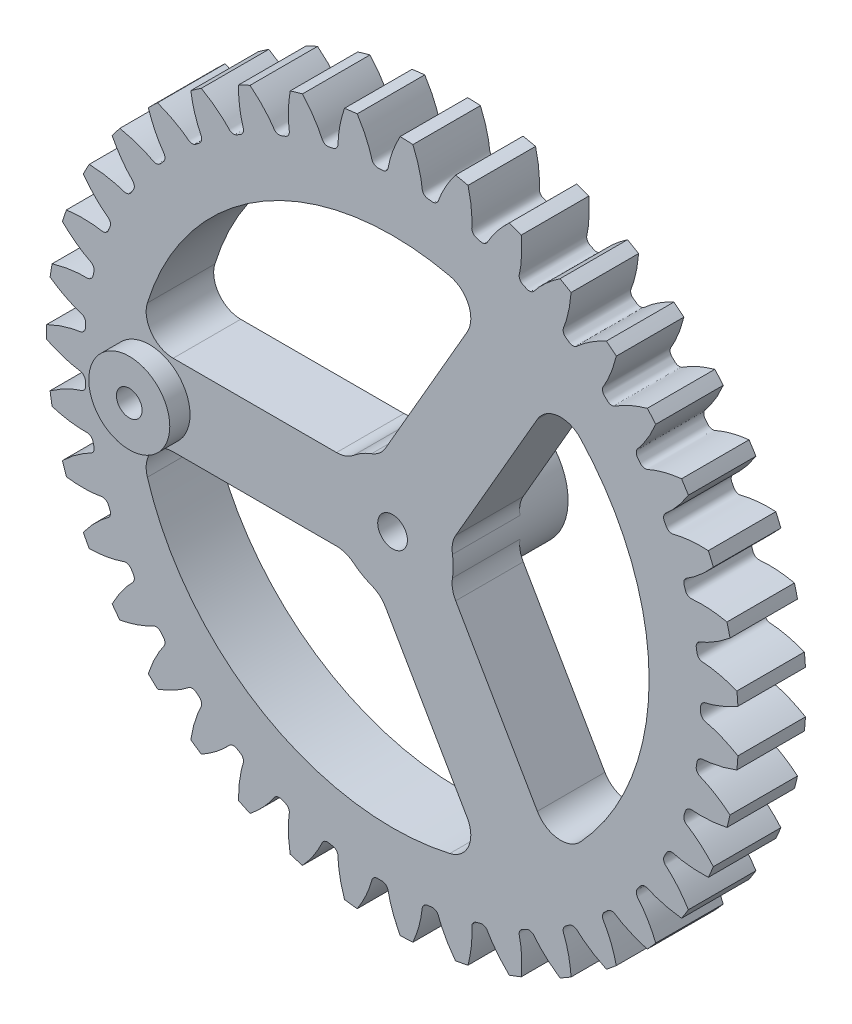
SolidWorks part; units mm, degrees
material "高韧性光敏树脂"
ref_plane "前视基准面" through (0, 0, 0) normal (0, 0, 1) x (1, 0, 0)
ref_plane "上视基准面" through (0, 0, 0) normal (0, 1, 0) x (1, 0, 0)
ref_plane "右视基准面" through (0, 0, 0) normal (1, 0, 0) x (0, 0, -1)
ref_axis "基准轴1" through (0, 0, 55) along (0, 0, -1)
sketch "SketchRevolveSpurGear2" plane through (0, 0, 0) normal (1, 0, 0) x (0, 0, -1)
  line L0 (0, 0) -> (1, 0) construction
  line L1 (-9.525, 0) -> (-9.525, 51.25)
  line L2 (-9.525, 51.25) -> (9.525, 51.25)
  line L3 (9.525, 51.25) -> (9.525, 0)
  line L4 (9.525, 0) -> (-9.525, 0)
revolve "SpurGear2" add sketch "SketchRevolveSpurGear2" angle 360 about L0
sketch "SketchToothSpurGear2" plane through (0, 0, 0) normal (0, 0, 1) x (1, 0, 0)
  arc A0 (51.2722, 3.2486) -> (51.2722, -3.2486) centre (0, 0) cw
  spline S0 degree 3 poles (51.2722, -3.2486) (50.9433, -3.0545) (50.5063, -2.811) (49.96, -2.5317) (49.6539, -2.3818) (49.3578, -2.2431) (49.0718, -2.1151) (48.7963, -1.9975) (48.5315, -1.8899) (48.2776, -1.7918) (48.035, -1.7028) (47.8039, -1.6225) (47.5844, -1.5505) (47.3768, -1.4864) (47.1813, -1.4298) (46.8338, -1.3346) (46.4965, -1.2659) (46.1788, -1.1645) (46.0425, -1.0887) (45.92, -0.9926) (45.8151, -0.8774) (45.7306, -0.7465) (45.6691, -0.6035) (45.6309, -0.4523) (45.6199, -0.2495) (45.6283, 0) (45.6199, 0.2495) (45.6309, 0.4523) (45.6691, 0.6035) (45.7306, 0.7465) (45.8151, 0.8774) (45.92, 0.9926) (46.0425, 1.0887) (46.1788, 1.1645) (46.4965, 1.2659) (46.8338, 1.3346) (47.1813, 1.4298) (47.3768, 1.4864) (47.5844, 1.5505) (47.8039, 1.6225) (48.035, 1.7028) (48.2776, 1.7918) (48.5315, 1.8899) (48.7963, 1.9975) (49.0718, 2.1151) (49.3578, 2.2431) (49.6539, 2.3818) (49.96, 2.5317) (50.5063, 2.811) (50.9433, 3.0545) (51.2722, 3.2486) knots 0 0 0 0 0.08292 0.108574 0.133236 0.156904 0.179579 0.201262 0.221951 0.241647 0.26035 0.27806 0.294777 0.310501 0.325231 0.338969 0.388722 0.399945 0.411168 0.422391 0.433614 0.444836 0.456059 0.467282 0.478505 0.5 0.521495 0.532718 0.543941 0.555164 0.566386 0.577609 0.588832 0.600055 0.611278 0.661031 0.674769 0.689499 0.705223 0.72194 0.73965 0.758353 0.778049 0.798738 0.820421 0.843096 0.866764 0.891426 0.91708 1 1 1 1
extrude "ToothExtrudeCutSpurGear2" cut sketch "SketchToothSpurGear2" against normal blind 9.525 and the other way blind 9.525
pattern_circular "PatternSpurGear2" count 39 every 9.231 about axis through (0, 0, 55) along (0, 0, -1) of "ToothExtrudeCutSpurGear2"
sketch "BoreRevolveSketch" plane through (0, 0, 0) normal (1, 0, 0) x (0, 0, -1)
  line L0 (0, 0) -> (1, 0) construction
  line L1 (-9.525, 0) -> (9.525, 0)
  line L2 (9.525, 0) -> (9.525, 1.5)
  line L3 (9.525, 1.5) -> (-9.525, 1.5)
  line L4 (-9.525, 1.5) -> (-9.525, 0)
  dimension "TaperSide1" = 1.5
  dimension "TaperSide2" = 1.5
revolve "BoreRevolveCut" cut sketch "BoreRevolveSketch" angle 360 about L0
sketch "AuxiliarySketchSpurGear2" plane through (0, 0, 0) normal (0, 0, 1) x (1, 0, 0)
  circle A0 centre (0, 0) radius 48.75 construction
  circle A1 centre (0, 0) radius 45.81 construction
  circle A2 centre (0, 0) radius 46.7525 construction
  circle A3 centre (0, 0) radius 51.25 construction
  circle A4 centre (0, 0) radius 45.625 construction
  dimension "PitchDiameter" = 97.5
  dimension "BaseDiameter" = 91.62
  dimension "FormDiameter" = 93.505
  dimension "MajorDiameter" = 102.5
  dimension "MinorDiameter" = 91.25
scale "缩放比例1" scale about origin uniform scaling yes scale factor 0.2
sketch "草图5" plane through (0, 0, 1.905) normal (0, 0, 1) x (1, 0, 0)
  arc A39 (0.2231, -10.2476) -> (0.6022, -10.2323) centre (0, 0) ccw
  arc A40 (1.8641, -10.0791) -> (2.2358, -10.0032) centre (0, 0) ccw
  arc A41 (3.4567, -9.6495) -> (3.8114, -9.515) centre (0, 0) ccw
  arc A42 (4.9598, -8.9701) -> (5.2884, -8.7804) centre (0, 0) ccw
  arc A43 (6.3345, -8.0583) -> (6.6284, -7.8184) centre (0, 0) ccw
  arc A44 (7.5451, -6.9378) -> (7.7967, -6.6539) centre (0, 0) ccw
  arc A45 (8.5603, -5.6377) -> (8.7631, -5.317) centre (0, 0) ccw
  arc A46 (9.3538, -4.1915) -> (9.5025, -3.8425) centre (0, 0) ccw
  arc A47 (9.9051, -2.6367) -> (9.9958, -2.2684) centre (0, 0) ccw
  arc A48 (10.1997, -1.0137) -> (10.2303, -0.6356) centre (0, 0) ccw
  arc A49 (10.2303, 0.6356) -> (10.1997, 1.0137) centre (0, 0) ccw
  arc A50 (9.9958, 2.2684) -> (9.9051, 2.6367) centre (0, 0) ccw
  arc A51 (9.5025, 3.8425) -> (9.3538, 4.1915) centre (0, 0) ccw
  arc A52 (8.7631, 5.317) -> (8.5603, 5.6377) centre (0, 0) ccw
  arc A53 (7.7967, 6.6539) -> (7.5451, 6.9378) centre (0, 0) ccw
  arc A54 (6.6284, 7.8184) -> (6.3345, 8.0583) centre (0, 0) ccw
  arc A55 (5.2884, 8.7804) -> (4.9598, 8.9701) centre (0, 0) ccw
  arc A56 (3.8114, 9.515) -> (3.4567, 9.6495) centre (0, 0) ccw
  arc A57 (2.2358, 10.0032) -> (1.8641, 10.0791) centre (0, 0) ccw
  arc A58 (0.6022, 10.2323) -> (0.2231, 10.2476) centre (0, 0) ccw
  arc A59 (-1.047, 10.1964) -> (-1.4236, 10.1507) centre (0, 0) ccw
  arc A60 (-2.669, 9.8964) -> (-3.0334, 9.7908) centre (0, 0) ccw
  arc A61 (-4.222, 9.3401) -> (-4.5647, 9.1775) centre (0, 0) ccw
  arc A62 (-5.6656, 8.5419) -> (-5.9778, 8.3264) centre (0, 0) ccw
  arc A63 (-6.9624, 7.5225) -> (-7.236, 7.2597) centre (0, 0) ccw
  arc A64 (-8.0789, 6.3082) -> (-8.3068, 6.0049) centre (0, 0) ccw
  arc A65 (-8.9862, 4.9306) -> (-9.1625, 4.5946) centre (0, 0) ccw
  arc A66 (-9.6608, 3.4252) -> (-9.7809, 3.0654) centre (0, 0) ccw
  arc A67 (-10.0851, 1.8312) -> (-10.146, 1.4567) centre (0, 0) ccw
  arc A68 (-10.2482, 0.1897) -> (-10.2482, -0.1897) centre (0, 0) ccw
  arc A69 (-10.146, -1.4567) -> (-10.0851, -1.8312) centre (0, 0) ccw
  arc A70 (-9.7809, -3.0654) -> (-9.6608, -3.4252) centre (0, 0) ccw
  arc A71 (-9.1625, -4.5946) -> (-8.9862, -4.9306) centre (0, 0) ccw
  arc A72 (-8.3068, -6.0049) -> (-8.0789, -6.3082) centre (0, 0) ccw
  arc A73 (-7.236, -7.2597) -> (-6.9624, -7.5225) centre (0, 0) ccw
  arc A74 (-5.9778, -8.3264) -> (-5.6656, -8.5419) centre (0, 0) ccw
  arc A75 (-4.5647, -9.1775) -> (-4.222, -9.3401) centre (0, 0) ccw
  arc A76 (-3.0334, -9.7908) -> (-2.669, -9.8964) centre (0, 0) ccw
  arc A77 (-1.4236, -10.1507) -> (-1.047, -10.1964) centre (0, 0) ccw
  arc A78 (0.2231, -10.2476) -> (0.6022, -10.2323) centre (0, 0) ccw
  arc A79 (1.8641, -10.0791) -> (2.2358, -10.0032) centre (0, 0) ccw
  arc A80 (3.4567, -9.6495) -> (3.8114, -9.515) centre (0, 0) ccw
  arc A81 (4.9598, -8.9701) -> (5.2884, -8.7804) centre (0, 0) ccw
  arc A82 (6.3345, -8.0583) -> (6.6284, -7.8184) centre (0, 0) ccw
  arc A83 (7.5451, -6.9378) -> (7.7967, -6.6539) centre (0, 0) ccw
  arc A84 (8.5603, -5.6377) -> (8.7631, -5.317) centre (0, 0) ccw
  arc A85 (9.3538, -4.1915) -> (9.5025, -3.8425) centre (0, 0) ccw
  arc A86 (9.9051, -2.6367) -> (9.9958, -2.2684) centre (0, 0) ccw
  arc A87 (10.1997, -1.0137) -> (10.2303, -0.6356) centre (0, 0) ccw
  arc A88 (10.2303, 0.6356) -> (10.1997, 1.0137) centre (0, 0) ccw
  arc A89 (9.9958, 2.2684) -> (9.9051, 2.6367) centre (0, 0) ccw
  arc A90 (9.5025, 3.8425) -> (9.3538, 4.1915) centre (0, 0) ccw
  arc A91 (8.7631, 5.317) -> (8.5603, 5.6377) centre (0, 0) ccw
  arc A92 (7.7967, 6.6539) -> (7.5451, 6.9378) centre (0, 0) ccw
  arc A93 (6.6284, 7.8184) -> (6.3345, 8.0583) centre (0, 0) ccw
  arc A94 (5.2884, 8.7804) -> (4.9598, 8.9701) centre (0, 0) ccw
  arc A95 (3.8114, 9.515) -> (3.4567, 9.6495) centre (0, 0) ccw
  arc A96 (2.2358, 10.0032) -> (1.8641, 10.0791) centre (0, 0) ccw
  arc A97 (0.6022, 10.2323) -> (0.2231, 10.2476) centre (0, 0) ccw
  arc A98 (-1.047, 10.1964) -> (-1.4236, 10.1507) centre (0, 0) ccw
  arc A99 (-2.669, 9.8964) -> (-3.0334, 9.7908) centre (0, 0) ccw
  arc A100 (-4.222, 9.3401) -> (-4.5647, 9.1775) centre (0, 0) ccw
  arc A101 (-5.6656, 8.5419) -> (-5.9778, 8.3264) centre (0, 0) ccw
  arc A102 (-6.9624, 7.5225) -> (-7.236, 7.2597) centre (0, 0) ccw
  arc A103 (-8.0789, 6.3082) -> (-8.3068, 6.0049) centre (0, 0) ccw
  arc A104 (-8.9862, 4.9306) -> (-9.1625, 4.5946) centre (0, 0) ccw
  arc A105 (-9.6608, 3.4252) -> (-9.7809, 3.0654) centre (0, 0) ccw
  arc A106 (-10.0851, 1.8312) -> (-10.146, 1.4567) centre (0, 0) ccw
  arc A107 (-10.2482, 0.1897) -> (-10.2482, -0.1897) centre (0, 0) ccw
  arc A108 (-10.146, -1.4567) -> (-10.0851, -1.8312) centre (0, 0) ccw
  arc A109 (-9.7809, -3.0654) -> (-9.6608, -3.4252) centre (0, 0) ccw
  arc A110 (-9.1625, -4.5946) -> (-8.9862, -4.9306) centre (0, 0) ccw
  arc A111 (-8.3068, -6.0049) -> (-8.0789, -6.3082) centre (0, 0) ccw
  arc A112 (-7.236, -7.2597) -> (-6.9624, -7.5225) centre (0, 0) ccw
  arc A113 (-5.9778, -8.3264) -> (-5.6656, -8.5419) centre (0, 0) ccw
  arc A114 (-4.5647, -9.1775) -> (-4.222, -9.3401) centre (0, 0) ccw
  arc A115 (-3.0334, -9.7908) -> (-2.669, -9.8964) centre (0, 0) ccw
  arc A116 (-1.4236, -10.1507) -> (-1.047, -10.1964) centre (0, 0) ccw
  spline S39 degree 3 poles (3980.2031, -395.6475) (-144.7935, 26.6662) (-10.7256, -27.3956) (-0.9083, -9.9635) (-0.8758, -9.9036) (-0.8457, -9.8455) (-0.8179, -9.7894) (-0.7921, -9.7353) (-0.7685, -9.6832) (-0.7469, -9.6333) (-0.7271, -9.5855) (-0.7092, -9.54) (-0.6931, -9.4967) (-0.6786, -9.4557) (-0.6657, -9.4171) (-0.6439, -9.3484) (-0.6274, -9.2816) (-0.6046, -9.2189) (-0.5883, -9.1923) (-0.5682, -9.1685) (-0.5443, -9.1485) (-0.5175, -9.1327) (-0.4884, -9.1216) (-0.4579, -9.1151) (-0.4173, -9.1146) (-0.3675, -9.1183) (-0.3175, -9.1186) (-0.2771, -9.1224) (-0.2472, -9.1313) (-0.2191, -9.1447) (-0.1936, -9.1627) (-0.1714, -9.1845) (-0.1532, -9.2098) (-0.1392, -9.2376) (-0.1215, -9.3019) (-0.1105, -9.3699) (-0.0942, -9.4401) (-0.0845, -9.4797) (-0.0734, -9.5216) (-0.0607, -9.5661) (-0.0466, -9.6129) (-0.0307, -9.6621) (-0.0132, -9.7136) (0.0062, -9.7674) (0.0275, -9.8234) (0.0508, -9.8816) (0.0761, -9.9419) (0.1036, -10.0043) (8.4863, -28.1697) (146.4675, 14.9279) (-3999.0301, -74.089) knots -21.586296 -21.586296 -21.586296 -21.586296 0.08292 0.108574 0.133236 0.156904 0.179579 0.201262 0.221951 0.241647 0.26035 0.27806 0.294777 0.310501 0.325231 0.338969 0.388722 0.399945 0.411168 0.422391 0.433614 0.444836 0.456059 0.467282 0.478505 0.5 0.521495 0.532718 0.543941 0.555164 0.566386 0.577609 0.588832 0.600055 0.611278 0.661031 0.674769 0.689499 0.705223 0.72194 0.73965 0.758353 0.778049 0.798738 0.820421 0.843096 0.866764 0.891426 0.91708 22.586117 22.586117 22.586117 22.586117 only from (-1.047, -10.1964) to (0.2231, -10.2476)
  spline S40 degree 3 poles (3992.1269, 247.9455) (-147.196, 3.0943) (-6.1922, -28.7613) (0.7018, -9.9802) (0.7241, -9.9158) (0.7445, -9.8537) (0.763, -9.7938) (0.7798, -9.7363) (0.7947, -9.6811) (0.8081, -9.6283) (0.8199, -9.578) (0.8303, -9.5302) (0.8393, -9.4849) (0.847, -9.4421) (0.8535, -9.4019) (0.8641, -9.3306) (0.8696, -9.262) (0.882, -9.1965) (0.8938, -9.1676) (0.9099, -9.141) (0.9303, -9.1174) (0.9542, -9.0974) (0.9811, -9.0818) (1.0102, -9.0705) (1.0502, -9.0635) (1.1, -9.0591) (1.1493, -9.0514) (1.1898, -9.0487) (1.2208, -9.0527) (1.2507, -9.0614) (1.2787, -9.0751) (1.3041, -9.0931) (1.3261, -9.1151) (1.3445, -9.1403) (1.3722, -9.201) (1.394, -9.2663) (1.4213, -9.333) (1.4372, -9.3704) (1.455, -9.4101) (1.4746, -9.4519) (1.4961, -9.4959) (1.5196, -9.5419) (1.5452, -9.59) (1.5729, -9.6399) (1.6029, -9.6918) (1.6352, -9.7455) (1.6699, -9.801) (1.707, -9.8581) (12.8952, -26.4436) (142.1761, 38.2297) (-3935.359, -714.6191) knots -21.586296 -21.586296 -21.586296 -21.586296 0.08292 0.108574 0.133236 0.156904 0.179579 0.201262 0.221951 0.241647 0.26035 0.27806 0.294777 0.310501 0.325231 0.338969 0.388722 0.399945 0.411168 0.422391 0.433614 0.444836 0.456059 0.467282 0.478505 0.5 0.521495 0.532718 0.543941 0.555164 0.566386 0.577609 0.588832 0.600055 0.611278 0.661031 0.674769 0.689499 0.705223 0.72194 0.73965 0.758353 0.778049 0.798738 0.820421 0.843096 0.866764 0.891426 0.91708 22.586117 22.586117 22.586117 22.586117 only from (0.6022, -10.2323) to (1.8641, -10.0791)
  spline S41 degree 3 poles (3900.6566, 885.1169) (-145.7863, -20.5577) (-1.4983, -29.3822) (2.2936, -9.7384) (2.3054, -9.6712) (2.3155, -9.6066) (2.3242, -9.5446) (2.3315, -9.4851) (2.3374, -9.4282) (2.3421, -9.374) (2.3457, -9.3224) (2.3483, -9.2736) (2.3499, -9.2274) (2.3507, -9.184) (2.3507, -9.1433) (2.3496, -9.0712) (2.344, -9.0026) (2.3458, -8.9359) (2.3528, -8.9055) (2.3645, -8.8766) (2.3808, -8.8501) (2.4012, -8.8266) (2.4253, -8.8068) (2.4522, -8.791) (2.4905, -8.7776) (2.5389, -8.7654) (2.5864, -8.7499) (2.6259, -8.7407) (2.6571, -8.7396) (2.688, -8.7435) (2.7179, -8.7524) (2.7458, -8.7662) (2.7711, -8.7843) (2.7933, -8.8063) (2.8304, -8.8617) (2.8624, -8.9227) (2.9, -8.9841) (2.9217, -9.0186) (2.9456, -9.0549) (2.9717, -9.093) (2.9999, -9.133) (3.0305, -9.1746) (3.0635, -9.2179) (3.0989, -9.2628) (3.1369, -9.3092) (3.1773, -9.357) (3.2205, -9.4062) (3.2663, -9.4566) (16.97, -24.0326) (134.2025, 60.5413) (-3769.7641, -1336.641) knots -21.586296 -21.586296 -21.586296 -21.586296 0.08292 0.108574 0.133236 0.156904 0.179579 0.201262 0.221951 0.241647 0.26035 0.27806 0.294777 0.310501 0.325231 0.338969 0.388722 0.399945 0.411168 0.422391 0.433614 0.444836 0.456059 0.467282 0.478505 0.5 0.521495 0.532718 0.543941 0.555164 0.566386 0.577609 0.588832 0.600055 0.611278 0.661031 0.674769 0.689499 0.705223 0.72194 0.73965 0.758353 0.778049 0.798738 0.820421 0.843096 0.866764 0.891426 0.91708 22.586117 22.586117 22.586117 22.586117 only from (2.2358, -10.0032) to (3.4567, -9.6495)
  spline S42 degree 3 poles (3708.1614, 1499.3642) (-140.6007, -43.6772) (3.2343, -29.242) (3.826, -9.2443) (3.8269, -9.1762) (3.8266, -9.1108) (3.8252, -9.0481) (3.8228, -8.9883) (3.8195, -8.9312) (3.8155, -8.8769) (3.8108, -8.8254) (3.8055, -8.7768) (3.7997, -8.731) (3.7934, -8.688) (3.7869, -8.6478) (3.7743, -8.5768) (3.7578, -8.51) (3.7489, -8.4439) (3.7509, -8.4128) (3.7577, -8.3824) (3.7696, -8.3536) (3.786, -8.3271) (3.8066, -8.3037) (3.8306, -8.2838) (3.8663, -8.2645) (3.9121, -8.2446) (3.9565, -8.2217) (3.994, -8.2063) (4.0246, -8.2002) (4.0558, -8.1991) (4.0867, -8.2031) (4.1165, -8.2122) (4.1443, -8.2261) (4.1697, -8.2442) (4.2153, -8.2929) (4.2566, -8.348) (4.3036, -8.4026) (4.3306, -8.4331) (4.36, -8.4651) (4.3918, -8.4986) (4.4261, -8.5335) (4.463, -8.5697) (4.5025, -8.6071) (4.5447, -8.6457) (4.5895, -8.6854) (4.6372, -8.7261) (4.6876, -8.7678) (4.7409, -8.8102) (20.6054, -20.9992) (122.7531, 81.2849) (-3506.5344, -1924.0445) knots -21.586296 -21.586296 -21.586296 -21.586296 0.08292 0.108574 0.133236 0.156904 0.179579 0.201262 0.221951 0.241647 0.26035 0.27806 0.294777 0.310501 0.325231 0.338969 0.388722 0.399945 0.411168 0.422391 0.433614 0.444836 0.456059 0.467282 0.478505 0.5 0.521495 0.532718 0.543941 0.555164 0.566386 0.577609 0.588832 0.600055 0.611278 0.661031 0.674769 0.689499 0.705223 0.72194 0.73965 0.758353 0.778049 0.798738 0.820421 0.843096 0.866764 0.891426 0.91708 22.586117 22.586117 22.586117 22.586117 only from (3.8114, -9.515) to (4.9598, -8.9701)
  spline S43 degree 3 poles (3419.6267, 2074.7787) (-131.7736, -65.6655) (7.8832, -28.3445) (5.2594, -8.5109) (5.2493, -8.4435) (5.2385, -8.379) (5.227, -8.3174) (5.2151, -8.2587) (5.2027, -8.2028) (5.19, -8.1499) (5.1771, -8.0999) (5.1641, -8.0527) (5.151, -8.0084) (5.138, -7.9669) (5.1251, -7.9283) (5.1013, -7.8603) (5.0742, -7.797) (5.0548, -7.7332) (5.0518, -7.7021) (5.0537, -7.6711) (5.0608, -7.6407) (5.0727, -7.6119) (5.0893, -7.5856) (5.1098, -7.5621) (5.1419, -7.5372) (5.184, -7.5103) (5.2241, -7.4805) (5.2587, -7.4593) (5.2879, -7.4484) (5.3185, -7.4423) (5.3496, -7.4413) (5.3805, -7.4455) (5.4102, -7.4548) (5.4382, -7.4686) (5.491, -7.5093) (5.5406, -7.5571) (5.5957, -7.6035) (5.6273, -7.6292) (5.6614, -7.6561) (5.6982, -7.684) (5.7377, -7.713) (5.7799, -7.7428) (5.8249, -7.7734) (5.8727, -7.8048) (5.9233, -7.8368) (5.9769, -7.8693) (6.0334, -7.9023) (6.0928, -7.9356) (23.707, -17.4219) (108.1245, 99.9232) (-3152.4872, -2461.6163) knots -21.586296 -21.586296 -21.586296 -21.586296 0.08292 0.108574 0.133236 0.156904 0.179579 0.201262 0.221951 0.241647 0.26035 0.27806 0.294777 0.310501 0.325231 0.338969 0.388722 0.399945 0.411168 0.422391 0.433614 0.444836 0.456059 0.467282 0.478505 0.5 0.521495 0.532718 0.543941 0.555164 0.566386 0.577609 0.588832 0.600055 0.611278 0.661031 0.674769 0.689499 0.705223 0.72194 0.73965 0.758353 0.778049 0.798738 0.820421 0.843096 0.866764 0.891426 0.91708 22.586117 22.586117 22.586117 22.586117 only from (5.2884, -8.7804) to (6.3345, -8.0583)
  spline S44 degree 3 poles (3042.5256, 2596.4576) (-119.5337, -85.9532) (12.3279, -26.7129) (6.5565, -7.557) (6.5357, -7.4921) (6.5147, -7.4302) (6.4936, -7.3712) (6.4723, -7.3151) (6.4512, -7.262) (6.4302, -7.2118) (6.4094, -7.1645) (6.3889, -7.12) (6.3689, -7.0784) (6.3494, -7.0396) (6.3305, -7.0035) (6.2961, -6.9402) (6.2593, -6.8821) (6.2299, -6.8222) (6.2219, -6.792) (6.2188, -6.761) (6.2209, -6.73) (6.2281, -6.6996) (6.2402, -6.6709) (6.2567, -6.6445) (6.2844, -6.6148) (6.3216, -6.5815) (6.3564, -6.5457) (6.3872, -6.5192) (6.4143, -6.5037) (6.4434, -6.4928) (6.474, -6.4868) (6.5052, -6.486) (6.536, -6.4904) (6.5658, -6.4995) (6.6244, -6.5313) (6.6811, -6.5704) (6.743, -6.6074) (6.7782, -6.6277) (6.8162, -6.6488) (6.857, -6.6705) (6.9006, -6.6927) (6.9471, -6.7153) (6.9964, -6.7384) (7.0486, -6.7617) (7.1037, -6.7851) (7.1618, -6.8086) (7.2229, -6.8321) (7.2869, -6.8555) (26.1947, -13.3934) (90.6955, 115.9736) (-2716.7923, -2935.4335) knots -21.586296 -21.586296 -21.586296 -21.586296 0.08292 0.108574 0.133236 0.156904 0.179579 0.201262 0.221951 0.241647 0.26035 0.27806 0.294777 0.310501 0.325231 0.338969 0.388722 0.399945 0.411168 0.422391 0.433614 0.444836 0.456059 0.467282 0.478505 0.5 0.521495 0.532718 0.543941 0.555164 0.566386 0.577609 0.588832 0.600055 0.611278 0.661031 0.674769 0.689499 0.705223 0.72194 0.73965 0.758353 0.778049 0.798738 0.820421 0.843096 0.866764 0.891426 0.91708 22.586117 22.586117 22.586117 22.586117 only from (6.6284, -7.8184) to (7.5451, -6.9378)
  spline S45 degree 3 poles (2586.6246, 3050.8896) (-104.1979, -104.0146) (16.4533, -24.3895) (7.6839, -6.4074) (7.6529, -6.3467) (7.6222, -6.2889) (7.5919, -6.2341) (7.562, -6.1822) (7.5326, -6.1332) (7.5038, -6.087) (7.4757, -6.0436) (7.4483, -6.003) (7.4219, -5.9651) (7.3964, -5.9299) (7.372, -5.8974) (7.3278, -5.8404) (7.2822, -5.7889) (7.2435, -5.7345) (7.2309, -5.706) (7.2228, -5.6759) (7.2199, -5.6449) (7.2221, -5.6138) (7.2295, -5.5836) (7.2415, -5.5548) (7.2641, -5.5211) (7.2954, -5.4822) (7.3241, -5.4413) (7.3502, -5.4102) (7.3745, -5.3906) (7.4015, -5.3751) (7.4307, -5.3643) (7.4613, -5.3585) (7.4925, -5.3579) (7.5234, -5.3621) (7.5864, -5.3841) (7.6485, -5.4136) (7.7155, -5.4402) (7.7536, -5.4546) (7.7945, -5.4693) (7.8382, -5.4841) (7.8848, -5.4991) (7.9343, -5.514) (7.9867, -5.5288) (8.042, -5.5434) (8.1002, -5.5577) (8.1613, -5.5716) (8.2253, -5.585) (8.2922, -5.5978) (28.004, -9.0181) (70.9175, 129.0204) (-2210.7339, -3333.2246) knots -21.586296 -21.586296 -21.586296 -21.586296 0.08292 0.108574 0.133236 0.156904 0.179579 0.201262 0.221951 0.241647 0.26035 0.27806 0.294777 0.310501 0.325231 0.338969 0.388722 0.399945 0.411168 0.422391 0.433614 0.444836 0.456059 0.467282 0.478505 0.5 0.521495 0.532718 0.543941 0.555164 0.566386 0.577609 0.588832 0.600055 0.611278 0.661031 0.674769 0.689499 0.705223 0.72194 0.73965 0.758353 0.778049 0.798738 0.820421 0.843096 0.866764 0.891426 0.91708 22.586117 22.586117 22.586117 22.586117 only from (7.7967, -6.6539) to (8.5603, -5.6377)
  spline S46 degree 3 poles (2063.7314, 3426.3051) (-86.1635, -119.3822) (20.1526, -21.4343) (8.6122, -5.0918) (8.5719, -5.0369) (8.5323, -4.9848) (8.4936, -4.9355) (8.4557, -4.8891) (8.4188, -4.8454) (8.383, -4.8045) (8.3483, -4.7661) (8.3148, -4.7304) (8.2827, -4.6973) (8.2519, -4.6666) (8.2225, -4.6385) (8.1698, -4.5893) (8.1165, -4.5458) (8.0696, -4.4983) (8.0525, -4.4722) (8.0398, -4.4438) (8.0319, -4.4136) (8.0291, -4.3826) (8.0315, -4.3516) (8.0388, -4.3212) (8.0557, -4.2843) (8.0804, -4.2409) (8.1021, -4.1959) (8.1229, -4.1611) (8.1437, -4.1378) (8.1679, -4.1182) (8.195, -4.1029) (8.2243, -4.0922) (8.2549, -4.0866) (8.2861, -4.0858) (8.3518, -4.0974) (8.4179, -4.1166) (8.4883, -4.1321) (8.5282, -4.1402) (8.5709, -4.1481) (8.6164, -4.1558) (8.6648, -4.163) (8.7161, -4.1698) (8.7702, -4.1761) (8.8271, -4.1816) (8.8868, -4.1864) (8.9493, -4.1903) (9.0147, -4.1933) (9.0828, -4.1952) (29.0879, -4.4091) (49.3029, 138.7256) (-1647.4187, -3644.6869) knots -21.586296 -21.586296 -21.586296 -21.586296 0.08292 0.108574 0.133236 0.156904 0.179579 0.201262 0.221951 0.241647 0.26035 0.27806 0.294777 0.310501 0.325231 0.338969 0.388722 0.399945 0.411168 0.422391 0.433614 0.444836 0.456059 0.467282 0.478505 0.5 0.521495 0.532718 0.543941 0.555164 0.566386 0.577609 0.588832 0.600055 0.611278 0.661031 0.674769 0.689499 0.705223 0.72194 0.73965 0.758353 0.778049 0.798738 0.820421 0.843096 0.866764 0.891426 0.91708 22.586117 22.586117 22.586117 22.586117 only from (8.7631, -5.317) to (9.3538, -4.1915)
  spline S47 degree 3 poles (1487.3886, 3712.9812) (-65.8974, -131.6578) (23.3299, -17.9241) (9.3174, -3.6444) (9.2689, -3.5966) (9.2215, -3.5515) (9.1753, -3.5092) (9.1305, -3.4694) (9.0871, -3.4322) (9.0451, -3.3975) (9.0047, -3.3653) (8.966, -3.3354) (8.9289, -3.3078) (8.8936, -3.2825) (8.8601, -3.2594) (8.8002, -3.2193) (8.7405, -3.1849) (8.6867, -3.1456) (8.6656, -3.1226) (8.6485, -3.0966) (8.6359, -3.0681) (8.6281, -3.0379) (8.6255, -3.0069) (8.6279, -2.9758) (8.6386, -2.9366) (8.656, -2.8898) (8.6702, -2.8419) (8.6852, -2.8042) (8.702, -2.7779) (8.7227, -2.7547) (8.747, -2.7352) (8.7742, -2.72) (8.8035, -2.7095) (8.8342, -2.7037) (8.9009, -2.7046) (8.9692, -2.713) (9.0412, -2.7169) (9.0819, -2.7186) (9.1253, -2.7195) (9.1715, -2.7198) (9.2204, -2.7192) (9.2721, -2.7177) (9.3265, -2.7151) (9.3835, -2.7115) (9.4432, -2.7066) (9.5056, -2.7005) (9.5706, -2.6929) (9.6381, -2.6839) (29.4185, 0.314) (26.4113, 144.8379) (-1041.4362, -3861.7537) knots -21.586296 -21.586296 -21.586296 -21.586296 0.08292 0.108574 0.133236 0.156904 0.179579 0.201262 0.221951 0.241647 0.26035 0.27806 0.294777 0.310501 0.325231 0.338969 0.388722 0.399945 0.411168 0.422391 0.433614 0.444836 0.456059 0.467282 0.478505 0.5 0.521495 0.532718 0.543941 0.555164 0.566386 0.577609 0.588832 0.600055 0.611278 0.661031 0.674769 0.689499 0.705223 0.72194 0.73965 0.758353 0.778049 0.798738 0.820421 0.843096 0.866764 0.891426 0.91708 22.586117 22.586117 22.586117 22.586117 only from (9.5025, -3.8425) to (9.9051, -2.6367)
  spline S48 degree 3 poles (872.5232, 3903.4929) (-43.9247, -140.5236) (25.903, -13.9496) (9.7814, -2.1026) (9.7258, -2.0632) (9.6718, -2.0263) (9.6194, -1.9919) (9.5688, -1.9598) (9.52, -1.9301) (9.473, -1.9026) (9.428, -1.8772) (9.3849, -1.854) (9.3439, -1.8327) (9.305, -1.8134) (9.2682, -1.7959) (9.2027, -1.766) (9.1383, -1.7416) (9.0788, -1.7114) (9.0543, -1.6921) (9.0332, -1.6692) (9.0162, -1.6431) (9.0037, -1.6145) (8.9962, -1.5843) (8.9935, -1.5532) (8.9978, -1.5129) (9.0075, -1.4639) (9.0138, -1.4143) (9.0225, -1.3747) (9.0349, -1.346) (9.0516, -1.3198) (9.0725, -1.2966) (9.0969, -1.2773) (9.1242, -1.2622) (9.1535, -1.2516) (9.2195, -1.2418) (9.2883, -1.2391) (9.3599, -1.2314) (9.4003, -1.2265) (9.4434, -1.2205) (9.489, -1.2134) (9.5372, -1.2049) (9.588, -1.1951) (9.6412, -1.1839) (9.697, -1.1712) (9.7551, -1.1568) (9.8157, -1.1407) (9.8786, -1.1228) (9.9438, -1.1031) (28.9872, 5.029) (2.8356, 147.1989) (-408.481, -3978.8031) knots -21.586296 -21.586296 -21.586296 -21.586296 0.08292 0.108574 0.133236 0.156904 0.179579 0.201262 0.221951 0.241647 0.26035 0.27806 0.294777 0.310501 0.325231 0.338969 0.388722 0.399945 0.411168 0.422391 0.433614 0.444836 0.456059 0.467282 0.478505 0.5 0.521495 0.532718 0.543941 0.555164 0.566386 0.577609 0.588832 0.600055 0.611278 0.661031 0.674769 0.689499 0.705223 0.72194 0.73965 0.758353 0.778049 0.798738 0.820421 0.843096 0.866764 0.891426 0.91708 22.586117 22.586117 22.586117 22.586117 only from (9.9958, -2.2684) to (10.1997, -1.0137)
  spline S49 degree 3 poles (235.06, 3992.9063) (-20.8143, -145.7498) (27.8052, -9.6138) (9.992, -0.5063) (9.9308, -0.4764) (9.8716, -0.4486) (9.8144, -0.423) (9.7593, -0.3995) (9.7063, -0.378) (9.6555, -0.3584) (9.607, -0.3406) (9.5608, -0.3245) (9.5169, -0.3101) (9.4754, -0.2973) (9.4363, -0.286) (9.3668, -0.2669) (9.2993, -0.2532) (9.2358, -0.2329) (9.2085, -0.2177) (9.184, -0.1985) (9.163, -0.1755) (9.1461, -0.1493) (9.1338, -0.1207) (9.1262, -0.0905) (9.124, -0.0499) (9.1257, 0) (9.124, 0.0499) (9.1262, 0.0905) (9.1338, 0.1207) (9.1461, 0.1493) (9.163, 0.1755) (9.184, 0.1985) (9.2085, 0.2177) (9.2358, 0.2329) (9.2993, 0.2532) (9.3668, 0.2669) (9.4363, 0.286) (9.4754, 0.2973) (9.5169, 0.3101) (9.5608, 0.3245) (9.607, 0.3406) (9.6555, 0.3584) (9.7063, 0.378) (9.7593, 0.3995) (9.8144, 0.423) (9.8716, 0.4486) (9.9308, 0.4764) (9.992, 0.5063) (27.8051, 9.6137) (-20.8135, 145.7476) (235.0536, -3992.8036) knots -21.586296 -21.586296 -21.586296 -21.586296 0.08292 0.108574 0.133236 0.156904 0.179579 0.201262 0.221951 0.241647 0.26035 0.27806 0.294777 0.310501 0.325231 0.338969 0.388722 0.399945 0.411168 0.422391 0.433614 0.444836 0.456059 0.467282 0.478505 0.5 0.521495 0.532718 0.543941 0.555164 0.566386 0.577609 0.588832 0.600055 0.611278 0.661031 0.674769 0.689499 0.705223 0.72194 0.73965 0.758353 0.778049 0.798738 0.820421 0.843096 0.866764 0.891426 0.91708 22.586117 22.586117 22.586117 22.586117 only from (10.2303, -0.6356) to (10.2303, 0.6356)
  spline S50 degree 3 poles (-408.4912, 3978.9055) (2.8352, -147.2013) (28.9873, -5.029) (9.9438, 1.1031) (9.8786, 1.1228) (9.8157, 1.1407) (9.7551, 1.1568) (9.697, 1.1712) (9.6412, 1.1839) (9.588, 1.1951) (9.5372, 1.2049) (9.489, 1.2134) (9.4434, 1.2205) (9.4003, 1.2265) (9.3599, 1.2314) (9.2883, 1.2391) (9.2195, 1.2418) (9.1535, 1.2516) (9.1242, 1.2622) (9.0969, 1.2773) (9.0725, 1.2966) (9.0516, 1.3198) (9.0349, 1.346) (9.0225, 1.3747) (9.0138, 1.4143) (9.0075, 1.4639) (8.9978, 1.5129) (8.9935, 1.5532) (8.9962, 1.5843) (9.0037, 1.6145) (9.0162, 1.6431) (9.0332, 1.6692) (9.0543, 1.6921) (9.0788, 1.7114) (9.1383, 1.7416) (9.2027, 1.766) (9.2682, 1.7959) (9.305, 1.8134) (9.3439, 1.8327) (9.3849, 1.854) (9.428, 1.8772) (9.473, 1.9026) (9.52, 1.9301) (9.5688, 1.9598) (9.6194, 1.9919) (9.6718, 2.0263) (9.7258, 2.0632) (9.7814, 2.1026) (25.9029, 13.9495) (-43.9235, 140.5215) (872.5005, -3903.3926) knots -21.586296 -21.586296 -21.586296 -21.586296 0.08292 0.108574 0.133236 0.156904 0.179579 0.201262 0.221951 0.241647 0.26035 0.27806 0.294777 0.310501 0.325231 0.338969 0.388722 0.399945 0.411168 0.422391 0.433614 0.444836 0.456059 0.467282 0.478505 0.5 0.521495 0.532718 0.543941 0.555164 0.566386 0.577609 0.588832 0.600055 0.611278 0.661031 0.674769 0.689499 0.705223 0.72194 0.73965 0.758353 0.778049 0.798738 0.820421 0.843096 0.866764 0.891426 0.91708 22.586117 22.586117 22.586117 22.586117 only from (10.1997, 1.0137) to (9.9958, 2.2684)
  spline S51 degree 3 poles (-1041.4627, 3861.8531) (26.4112, -144.8403) (29.4187, -0.314) (9.6381, 2.6839) (9.5706, 2.6929) (9.5056, 2.7005) (9.4432, 2.7066) (9.3835, 2.7115) (9.3265, 2.7151) (9.2721, 2.7177) (9.2204, 2.7192) (9.1715, 2.7198) (9.1253, 2.7195) (9.0819, 2.7186) (9.0412, 2.7169) (8.9692, 2.713) (8.9009, 2.7046) (8.8342, 2.7037) (8.8035, 2.7095) (8.7742, 2.72) (8.747, 2.7352) (8.7227, 2.7547) (8.702, 2.7779) (8.6852, 2.8042) (8.6702, 2.8419) (8.656, 2.8898) (8.6386, 2.9366) (8.6279, 2.9758) (8.6255, 3.0069) (8.6281, 3.0379) (8.6359, 3.0681) (8.6485, 3.0966) (8.6656, 3.1226) (8.6867, 3.1456) (8.7405, 3.1849) (8.8002, 3.2193) (8.8601, 3.2594) (8.8936, 3.2825) (8.9289, 3.3078) (8.966, 3.3354) (9.0047, 3.3653) (9.0451, 3.3975) (9.0871, 3.4322) (9.1305, 3.4694) (9.1753, 3.5092) (9.2215, 3.5515) (9.2689, 3.5966) (9.3174, 3.6444) (23.3298, 17.924) (-65.8959, 131.6559) (1487.35, -3712.8857) knots -21.586296 -21.586296 -21.586296 -21.586296 0.08292 0.108574 0.133236 0.156904 0.179579 0.201262 0.221951 0.241647 0.26035 0.27806 0.294777 0.310501 0.325231 0.338969 0.388722 0.399945 0.411168 0.422391 0.433614 0.444836 0.456059 0.467282 0.478505 0.5 0.521495 0.532718 0.543941 0.555164 0.566386 0.577609 0.588832 0.600055 0.611278 0.661031 0.674769 0.689499 0.705223 0.72194 0.73965 0.758353 0.778049 0.798738 0.820421 0.843096 0.866764 0.891426 0.91708 22.586117 22.586117 22.586117 22.586117 only from (9.9051, 2.6367) to (9.5025, 3.8425)
  spline S52 degree 3 poles (-1647.4608, 3644.7808) (49.3032, -138.728) (29.0881, 4.4091) (9.0828, 4.1952) (9.0147, 4.1933) (8.9493, 4.1903) (8.8868, 4.1864) (8.8271, 4.1816) (8.7702, 4.1761) (8.7161, 4.1698) (8.6648, 4.163) (8.6164, 4.1558) (8.5709, 4.1481) (8.5282, 4.1402) (8.4883, 4.1321) (8.4179, 4.1166) (8.3518, 4.0974) (8.2861, 4.0858) (8.2549, 4.0866) (8.2243, 4.0922) (8.195, 4.1029) (8.1679, 4.1182) (8.1437, 4.1378) (8.1229, 4.1611) (8.1021, 4.1959) (8.0804, 4.2409) (8.0557, 4.2843) (8.0388, 4.3212) (8.0315, 4.3516) (8.0291, 4.3826) (8.0319, 4.4136) (8.0398, 4.4438) (8.0525, 4.4722) (8.0696, 4.4983) (8.1165, 4.5458) (8.1698, 4.5893) (8.2225, 4.6385) (8.2519, 4.6666) (8.2827, 4.6973) (8.3148, 4.7304) (8.3483, 4.7661) (8.383, 4.8045) (8.4188, 4.8454) (8.4557, 4.8891) (8.4936, 4.9355) (8.5323, 4.9848) (8.5719, 5.0369) (8.6122, 5.0918) (20.1525, 21.4342) (-86.1617, 119.3806) (2063.678, -3426.2171) knots -21.586296 -21.586296 -21.586296 -21.586296 0.08292 0.108574 0.133236 0.156904 0.179579 0.201262 0.221951 0.241647 0.26035 0.27806 0.294777 0.310501 0.325231 0.338969 0.388722 0.399945 0.411168 0.422391 0.433614 0.444836 0.456059 0.467282 0.478505 0.5 0.521495 0.532718 0.543941 0.555164 0.566386 0.577609 0.588832 0.600055 0.611278 0.661031 0.674769 0.689499 0.705223 0.72194 0.73965 0.758353 0.778049 0.798738 0.820421 0.843096 0.866764 0.891426 0.91708 22.586117 22.586117 22.586117 22.586117 only from (9.3538, 4.1915) to (8.7631, 5.317)
  spline S53 degree 3 poles (-2210.7906, 3333.3105) (70.9183, -129.0227) (28.0041, 9.0181) (8.2922, 5.5978) (8.2253, 5.585) (8.1613, 5.5716) (8.1002, 5.5577) (8.042, 5.5434) (7.9867, 5.5288) (7.9343, 5.514) (7.8848, 5.4991) (7.8382, 5.4841) (7.7945, 5.4693) (7.7536, 5.4546) (7.7155, 5.4402) (7.6485, 5.4136) (7.5864, 5.3841) (7.5234, 5.3621) (7.4925, 5.3579) (7.4613, 5.3585) (7.4307, 5.3643) (7.4015, 5.3751) (7.3745, 5.3906) (7.3502, 5.4102) (7.3241, 5.4413) (7.2954, 5.4822) (7.2641, 5.5211) (7.2415, 5.5548) (7.2295, 5.5836) (7.2221, 5.6138) (7.2199, 5.6449) (7.2228, 5.6759) (7.2309, 5.706) (7.2435, 5.7345) (7.2822, 5.7889) (7.3278, 5.8404) (7.372, 5.8974) (7.3964, 5.9299) (7.4219, 5.9651) (7.4483, 6.003) (7.4757, 6.0436) (7.5038, 6.087) (7.5326, 6.1332) (7.562, 6.1822) (7.5919, 6.2341) (7.6222, 6.2889) (7.6529, 6.3467) (7.6839, 6.4074) (16.4532, 24.3893) (-104.1959, 104.0133) (2586.5578, -3050.8113) knots -21.586296 -21.586296 -21.586296 -21.586296 0.08292 0.108574 0.133236 0.156904 0.179579 0.201262 0.221951 0.241647 0.26035 0.27806 0.294777 0.310501 0.325231 0.338969 0.388722 0.399945 0.411168 0.422391 0.433614 0.444836 0.456059 0.467282 0.478505 0.5 0.521495 0.532718 0.543941 0.555164 0.566386 0.577609 0.588832 0.600055 0.611278 0.661031 0.674769 0.689499 0.705223 0.72194 0.73965 0.758353 0.778049 0.798738 0.820421 0.843096 0.866764 0.891426 0.91708 22.586117 22.586117 22.586117 22.586117 only from (8.5603, 5.6377) to (7.7967, 6.6539)
  spline S54 degree 3 poles (-2716.862, 2935.5093) (90.6966, -115.9758) (26.1949, 13.3935) (7.2869, 6.8555) (7.2229, 6.8321) (7.1618, 6.8086) (7.1037, 6.7851) (7.0486, 6.7617) (6.9964, 6.7384) (6.9471, 6.7153) (6.9006, 6.6927) (6.857, 6.6705) (6.8162, 6.6488) (6.7782, 6.6277) (6.743, 6.6074) (6.6811, 6.5704) (6.6244, 6.5313) (6.5658, 6.4995) (6.536, 6.4904) (6.5052, 6.486) (6.474, 6.4868) (6.4434, 6.4928) (6.4143, 6.5037) (6.3872, 6.5192) (6.3564, 6.5457) (6.3216, 6.5815) (6.2844, 6.6148) (6.2567, 6.6445) (6.2402, 6.6709) (6.2281, 6.6996) (6.2209, 6.73) (6.2188, 6.761) (6.2219, 6.792) (6.2299, 6.8222) (6.2593, 6.8821) (6.2961, 6.9402) (6.3305, 7.0035) (6.3494, 7.0396) (6.3689, 7.0784) (6.3889, 7.12) (6.4094, 7.1645) (6.4302, 7.2118) (6.4512, 7.262) (6.4723, 7.3151) (6.4936, 7.3712) (6.5147, 7.4302) (6.5357, 7.4921) (6.5565, 7.557) (12.3278, 26.7128) (-119.5315, 85.9522) (3042.4471, -2596.391) knots -21.586296 -21.586296 -21.586296 -21.586296 0.08292 0.108574 0.133236 0.156904 0.179579 0.201262 0.221951 0.241647 0.26035 0.27806 0.294777 0.310501 0.325231 0.338969 0.388722 0.399945 0.411168 0.422391 0.433614 0.444836 0.456059 0.467282 0.478505 0.5 0.521495 0.532718 0.543941 0.555164 0.566386 0.577609 0.588832 0.600055 0.611278 0.661031 0.674769 0.689499 0.705223 0.72194 0.73965 0.758353 0.778049 0.798738 0.820421 0.843096 0.866764 0.891426 0.91708 22.586117 22.586117 22.586117 22.586117 only from (7.5451, 6.9378) to (6.6284, 7.8184)
  spline S55 degree 3 poles (-3152.5682, 2461.6799) (108.1259, -99.9252) (23.7072, 17.422) (6.0928, 7.9356) (6.0334, 7.9023) (5.9769, 7.8693) (5.9233, 7.8368) (5.8727, 7.8048) (5.8249, 7.7734) (5.7799, 7.7428) (5.7377, 7.713) (5.6982, 7.684) (5.6614, 7.6561) (5.6273, 7.6292) (5.5957, 7.6035) (5.5406, 7.5571) (5.491, 7.5093) (5.4382, 7.4686) (5.4102, 7.4548) (5.3805, 7.4455) (5.3496, 7.4413) (5.3185, 7.4423) (5.2879, 7.4484) (5.2587, 7.4593) (5.2241, 7.4805) (5.184, 7.5103) (5.1419, 7.5372) (5.1098, 7.5621) (5.0893, 7.5856) (5.0727, 7.6119) (5.0608, 7.6407) (5.0537, 7.6711) (5.0518, 7.7021) (5.0548, 7.7332) (5.0742, 7.797) (5.1013, 7.8603) (5.1251, 7.9283) (5.138, 7.9669) (5.151, 8.0084) (5.1641, 8.0527) (5.1771, 8.0999) (5.19, 8.1499) (5.2027, 8.2028) (5.2151, 8.2587) (5.227, 8.3174) (5.2385, 8.379) (5.2493, 8.4435) (5.2594, 8.5109) (7.8832, 28.3444) (-131.7713, 65.6649) (3419.5386, -2074.7256) knots -21.586296 -21.586296 -21.586296 -21.586296 0.08292 0.108574 0.133236 0.156904 0.179579 0.201262 0.221951 0.241647 0.26035 0.27806 0.294777 0.310501 0.325231 0.338969 0.388722 0.399945 0.411168 0.422391 0.433614 0.444836 0.456059 0.467282 0.478505 0.5 0.521495 0.532718 0.543941 0.555164 0.566386 0.577609 0.588832 0.600055 0.611278 0.661031 0.674769 0.689499 0.705223 0.72194 0.73965 0.758353 0.778049 0.798738 0.820421 0.843096 0.866764 0.891426 0.91708 22.586117 22.586117 22.586117 22.586117 only from (6.3345, 8.0583) to (5.2884, 8.7804)
  spline S56 degree 3 poles (-3506.6245, 1924.0943) (122.7548, -81.2865) (20.6055, 20.9993) (4.7409, 8.8102) (4.6876, 8.7678) (4.6372, 8.7261) (4.5895, 8.6854) (4.5447, 8.6457) (4.5025, 8.6071) (4.463, 8.5697) (4.4261, 8.5335) (4.3918, 8.4986) (4.36, 8.4651) (4.3306, 8.4331) (4.3036, 8.4026) (4.2566, 8.348) (4.2153, 8.2929) (4.1697, 8.2442) (4.1443, 8.2261) (4.1165, 8.2122) (4.0867, 8.2031) (4.0558, 8.1991) (4.0246, 8.2002) (3.994, 8.2063) (3.9565, 8.2217) (3.9121, 8.2446) (3.8663, 8.2645) (3.8306, 8.2838) (3.8066, 8.3037) (3.786, 8.3271) (3.7696, 8.3536) (3.7577, 8.3824) (3.7509, 8.4128) (3.7489, 8.4439) (3.7578, 8.51) (3.7743, 8.5768) (3.7869, 8.6478) (3.7934, 8.688) (3.7997, 8.731) (3.8055, 8.7768) (3.8108, 8.8254) (3.8155, 8.8769) (3.8195, 8.9312) (3.8228, 8.9883) (3.8252, 9.0481) (3.8266, 9.1108) (3.8269, 9.1762) (3.826, 9.2443) (3.2343, 29.2419) (-140.5983, 43.677) (3708.0659, -1499.3259) knots -21.586296 -21.586296 -21.586296 -21.586296 0.08292 0.108574 0.133236 0.156904 0.179579 0.201262 0.221951 0.241647 0.26035 0.27806 0.294777 0.310501 0.325231 0.338969 0.388722 0.399945 0.411168 0.422391 0.433614 0.444836 0.456059 0.467282 0.478505 0.5 0.521495 0.532718 0.543941 0.555164 0.566386 0.577609 0.588832 0.600055 0.611278 0.661031 0.674769 0.689499 0.705223 0.72194 0.73965 0.758353 0.778049 0.798738 0.820421 0.843096 0.866764 0.891426 0.91708 22.586117 22.586117 22.586117 22.586117 only from (4.9598, 8.9701) to (3.8114, 9.515)
  spline S57 degree 3 poles (-3769.861, 1336.6756) (134.2045, -60.5426) (16.9701, 24.0327) (3.2663, 9.4566) (3.2205, 9.4062) (3.1773, 9.357) (3.1369, 9.3092) (3.0989, 9.2628) (3.0635, 9.2179) (3.0305, 9.1746) (2.9999, 9.133) (2.9717, 9.093) (2.9456, 9.0549) (2.9217, 9.0186) (2.9, 8.9841) (2.8624, 8.9227) (2.8304, 8.8617) (2.7933, 8.8063) (2.7711, 8.7843) (2.7458, 8.7662) (2.7179, 8.7524) (2.688, 8.7435) (2.6571, 8.7396) (2.6259, 8.7407) (2.5864, 8.7499) (2.5389, 8.7654) (2.4905, 8.7776) (2.4522, 8.791) (2.4253, 8.8068) (2.4012, 8.8266) (2.3808, 8.8501) (2.3645, 8.8766) (2.3528, 8.9055) (2.3458, 8.9359) (2.344, 9.0026) (2.3496, 9.0712) (2.3507, 9.1433) (2.3507, 9.184) (2.3499, 9.2274) (2.3483, 9.2736) (2.3457, 9.3224) (2.3421, 9.374) (2.3374, 9.4282) (2.3315, 9.4851) (2.3242, 9.5446) (2.3155, 9.6066) (2.3054, 9.6712) (2.2936, 9.7384) (-1.4983, 29.382) (-145.7839, 20.5578) (3900.5562, -885.0944) knots -21.586296 -21.586296 -21.586296 -21.586296 0.08292 0.108574 0.133236 0.156904 0.179579 0.201262 0.221951 0.241647 0.26035 0.27806 0.294777 0.310501 0.325231 0.338969 0.388722 0.399945 0.411168 0.422391 0.433614 0.444836 0.456059 0.467282 0.478505 0.5 0.521495 0.532718 0.543941 0.555164 0.566386 0.577609 0.588832 0.600055 0.611278 0.661031 0.674769 0.689499 0.705223 0.72194 0.73965 0.758353 0.778049 0.798738 0.820421 0.843096 0.866764 0.891426 0.91708 22.586117 22.586117 22.586117 22.586117 only from (3.4567, 9.6495) to (2.2358, 10.0032)
  spline S58 degree 3 poles (-3935.4602, 714.6378) (142.1783, -38.2307) (12.8953, 26.4437) (1.707, 9.8581) (1.6699, 9.801) (1.6352, 9.7455) (1.6029, 9.6918) (1.5729, 9.6399) (1.5452, 9.59) (1.5196, 9.5419) (1.4961, 9.4959) (1.4746, 9.4519) (1.455, 9.4101) (1.4372, 9.3704) (1.4213, 9.333) (1.394, 9.2663) (1.3722, 9.201) (1.3445, 9.1403) (1.3261, 9.1151) (1.3041, 9.0931) (1.2787, 9.0751) (1.2507, 9.0614) (1.2208, 9.0527) (1.1898, 9.0487) (1.1493, 9.0514) (1.1, 9.0591) (1.0502, 9.0635) (1.0102, 9.0705) (0.9811, 9.0818) (0.9542, 9.0974) (0.9303, 9.1174) (0.9099, 9.141) (0.8938, 9.1676) (0.882, 9.1965) (0.8696, 9.262) (0.8641, 9.3306) (0.8535, 9.4019) (0.847, 9.4421) (0.8393, 9.4849) (0.8303, 9.5302) (0.8199, 9.578) (0.8081, 9.6283) (0.7947, 9.6811) (0.7798, 9.7363) (0.763, 9.7938) (0.7445, 9.8537) (0.7241, 9.9158) (0.7018, 9.9802) (-6.1921, 28.7612) (-147.1937, -3.0938) (3992.0241, -247.9395) knots -21.586296 -21.586296 -21.586296 -21.586296 0.08292 0.108574 0.133236 0.156904 0.179579 0.201262 0.221951 0.241647 0.26035 0.27806 0.294777 0.310501 0.325231 0.338969 0.388722 0.399945 0.411168 0.422391 0.433614 0.444836 0.456059 0.467282 0.478505 0.5 0.521495 0.532718 0.543941 0.555164 0.566386 0.577609 0.588832 0.600055 0.611278 0.661031 0.674769 0.689499 0.705223 0.72194 0.73965 0.758353 0.778049 0.798738 0.820421 0.843096 0.866764 0.891426 0.91708 22.586117 22.586117 22.586117 22.586117 only from (1.8641, 10.0791) to (0.6022, 10.2323)
  spline S59 degree 3 poles (-3999.133, 74.0912) (146.4697, -14.9287) (8.4864, 28.1698) (0.1036, 10.0043) (0.0761, 9.9419) (0.0508, 9.8816) (0.0275, 9.8234) (0.0062, 9.7674) (-0.0132, 9.7136) (-0.0307, 9.6621) (-0.0466, 9.6129) (-0.0607, 9.5661) (-0.0734, 9.5216) (-0.0845, 9.4797) (-0.0942, 9.4401) (-0.1105, 9.3699) (-0.1215, 9.3019) (-0.1392, 9.2376) (-0.1532, 9.2098) (-0.1714, 9.1845) (-0.1936, 9.1627) (-0.2191, 9.1447) (-0.2472, 9.1313) (-0.2771, 9.1224) (-0.3175, 9.1186) (-0.3675, 9.1183) (-0.4173, 9.1146) (-0.4579, 9.1151) (-0.4884, 9.1216) (-0.5175, 9.1327) (-0.5443, 9.1485) (-0.5682, 9.1685) (-0.5883, 9.1923) (-0.6046, 9.2189) (-0.6274, 9.2816) (-0.6439, 9.3484) (-0.6657, 9.4171) (-0.6786, 9.4557) (-0.6931, 9.4967) (-0.7092, 9.54) (-0.7271, 9.5855) (-0.7469, 9.6333) (-0.7685, 9.6832) (-0.7921, 9.7353) (-0.8179, 9.7894) (-0.8457, 9.8455) (-0.8758, 9.9036) (-0.9083, 9.9635) (-10.7255, 27.3954) (-144.7913, -26.6653) (3980.1007, 395.637) knots -21.586296 -21.586296 -21.586296 -21.586296 0.08292 0.108574 0.133236 0.156904 0.179579 0.201262 0.221951 0.241647 0.26035 0.27806 0.294777 0.310501 0.325231 0.338969 0.388722 0.399945 0.411168 0.422391 0.433614 0.444836 0.456059 0.467282 0.478505 0.5 0.521495 0.532718 0.543941 0.555164 0.566386 0.577609 0.588832 0.600055 0.611278 0.661031 0.674769 0.689499 0.705223 0.72194 0.73965 0.758353 0.778049 0.798738 0.820421 0.843096 0.866764 0.891426 0.91708 22.586117 22.586117 22.586117 22.586117 only from (0.2231, 10.2476) to (-1.047, 10.1964)
  spline S60 degree 3 poles (-3959.2303, -568.3743) (146.9677, 8.7601) (3.8577, 29.1663) (-1.5026, 9.8913) (-1.5197, 9.8254) (-1.535, 9.7618) (-1.5486, 9.7006) (-1.5607, 9.6419) (-1.5712, 9.5857) (-1.5802, 9.5321) (-1.588, 9.481) (-1.5945, 9.4325) (-1.5998, 9.3866) (-1.6041, 9.3433) (-1.6073, 9.3028) (-1.6121, 9.2309) (-1.612, 9.162) (-1.6192, 9.0957) (-1.6286, 9.0659) (-1.6425, 9.0381) (-1.6609, 9.0129) (-1.6832, 8.9911) (-1.7087, 8.9734) (-1.7368, 8.9598) (-1.7761, 8.9496) (-1.8254, 8.9412) (-1.8739, 8.9296) (-1.9141, 8.9236) (-1.9453, 8.9251) (-1.9757, 8.9314) (-2.0048, 8.9427) (-2.0315, 8.9587) (-2.0553, 8.9788) (-2.0756, 9.0025) (-2.1082, 9.0607) (-2.1351, 9.1241) (-2.1677, 9.1884) (-2.1866, 9.2244) (-2.2075, 9.2625) (-2.2303, 9.3026) (-2.2553, 9.3447) (-2.2825, 9.3887) (-2.3118, 9.4345) (-2.3435, 9.4821) (-2.3776, 9.5314) (-2.4141, 9.5823) (-2.4531, 9.6348) (-2.4948, 9.6888) (-14.9812, 25.3202) (-138.6389, -49.5461) (3865.0949, 1028.9667) knots -21.586296 -21.586296 -21.586296 -21.586296 0.08292 0.108574 0.133236 0.156904 0.179579 0.201262 0.221951 0.241647 0.26035 0.27806 0.294777 0.310501 0.325231 0.338969 0.388722 0.399945 0.411168 0.422391 0.433614 0.444836 0.456059 0.467282 0.478505 0.5 0.521495 0.532718 0.543941 0.555164 0.566386 0.577609 0.588832 0.600055 0.611278 0.661031 0.674769 0.689499 0.705223 0.72194 0.73965 0.758353 0.778049 0.798738 0.820421 0.843096 0.866764 0.891426 0.91708 22.586117 22.586117 22.586117 22.586117 only from (-1.4236, 10.1507) to (-2.669, 9.8964)
  spline S61 degree 3 poles (-3816.7857, -1196.1192) (143.6593, 32.2219) (-0.8708, 29.4075) (-3.0698, 9.5222) (-3.0761, 9.4544) (-3.081, 9.3892) (-3.0847, 9.3266) (-3.0871, 9.2667) (-3.0885, 9.2096) (-3.0888, 9.1551) (-3.0883, 9.1035) (-3.0869, 9.0545) (-3.0848, 9.0084) (-3.0821, 8.965) (-3.0788, 8.9245) (-3.0719, 8.8527) (-3.0608, 8.7848) (-3.0573, 8.7182) (-3.0618, 8.6873) (-3.0711, 8.6576) (-3.0852, 8.6298) (-3.1037, 8.6047) (-3.126, 8.5831) (-3.1516, 8.5652) (-3.1887, 8.5488) (-3.236, 8.5326) (-3.2821, 8.5134) (-3.3208, 8.501) (-3.3518, 8.4975) (-3.3829, 8.4988) (-3.4133, 8.5054) (-3.4423, 8.5168) (-3.469, 8.5329) (-3.4928, 8.553) (-3.5343, 8.6052) (-3.5711, 8.6634) (-3.6135, 8.7217) (-3.638, 8.7542) (-3.6647, 8.7885) (-3.6937, 8.8244) (-3.7251, 8.8619) (-3.759, 8.901) (-3.7953, 8.9415) (-3.8342, 8.9834) (-3.8758, 9.0266) (-3.92, 9.071) (-3.9669, 9.1165) (-4.0166, 9.1631) (-18.8488, 22.5891) (-128.8958, -71.1438) (3649.985, 1635.6466) knots -21.586296 -21.586296 -21.586296 -21.586296 0.08292 0.108574 0.133236 0.156904 0.179579 0.201262 0.221951 0.241647 0.26035 0.27806 0.294777 0.310501 0.325231 0.338969 0.388722 0.399945 0.411168 0.422391 0.433614 0.444836 0.456059 0.467282 0.478505 0.5 0.521495 0.532718 0.543941 0.555164 0.566386 0.577609 0.588832 0.600055 0.611278 0.661031 0.674769 0.689499 0.705223 0.72194 0.73965 0.758353 0.778049 0.798738 0.820421 0.843096 0.866764 0.891426 0.91708 22.586117 22.586117 22.586117 22.586117 only from (-3.0334, 9.7908) to (-4.222, 9.3401)
  spline S62 degree 3 poles (-3575.4883, -1792.8852) (136.6302, 54.8492) (-5.5768, 28.8869) (-4.5575, 8.9065) (-4.5529, 8.8385) (-4.5473, 8.7733) (-4.5408, 8.711) (-4.5336, 8.6515) (-4.5258, 8.5949) (-4.5174, 8.5411) (-4.5086, 8.4902) (-4.4994, 8.4421) (-4.4899, 8.3969) (-4.4802, 8.3545) (-4.4705, 8.315) (-4.4522, 8.2453) (-4.4304, 8.18) (-4.4162, 8.1149) (-4.4157, 8.0837) (-4.4201, 8.0528) (-4.4295, 8.0231) (-4.4438, 7.9954) (-4.4624, 7.9705) (-4.4848, 7.9487) (-4.5188, 7.9266) (-4.5628, 7.9031) (-4.6052, 7.8766) (-4.6414, 7.8583) (-4.6714, 7.8498) (-4.7024, 7.8461) (-4.7335, 7.8477) (-4.7639, 7.8543) (-4.7928, 7.8659) (-4.8196, 7.8819) (-4.8689, 7.9268) (-4.9145, 7.9784) (-4.9658, 8.0291) (-4.9951, 8.0573) (-5.027, 8.0868) (-5.0614, 8.1176) (-5.0984, 8.1496) (-5.1381, 8.1828) (-5.1805, 8.2169) (-5.2256, 8.252) (-5.2735, 8.288) (-5.3243, 8.3247) (-5.3779, 8.3621) (-5.4345, 8.4002) (-22.2283, 19.2731) (-115.8144, -90.8988) (3340.3425, 2199.9642) knots -21.586296 -21.586296 -21.586296 -21.586296 0.08292 0.108574 0.133236 0.156904 0.179579 0.201262 0.221951 0.241647 0.26035 0.27806 0.294777 0.310501 0.325231 0.338969 0.388722 0.399945 0.411168 0.422391 0.433614 0.444836 0.456059 0.467282 0.478505 0.5 0.521495 0.532718 0.543941 0.555164 0.566386 0.577609 0.588832 0.600055 0.611278 0.661031 0.674769 0.689499 0.705223 0.72194 0.73965 0.758353 0.778049 0.798738 0.820421 0.843096 0.866764 0.891426 0.91708 22.586117 22.586117 22.586117 22.586117 only from (-4.5647, 9.1775) to (-5.6656, 8.5419)
  spline S63 degree 3 poles (-3241.5876, -2343.2165) (126.0624, 76.056) (-10.1384, 27.6183) (-5.9272, 8.0601) (-5.9117, 7.9937) (-5.8957, 7.9303) (-5.8794, 7.8698) (-5.8627, 7.8122) (-5.8459, 7.7576) (-5.829, 7.7059) (-5.8121, 7.657) (-5.7953, 7.6111) (-5.7787, 7.5679) (-5.7624, 7.5277) (-5.7464, 7.4902) (-5.7172, 7.4244) (-5.6852, 7.3634) (-5.6607, 7.3014) (-5.6552, 7.2706) (-5.6546, 7.2395) (-5.6592, 7.2087) (-5.6688, 7.1791) (-5.6832, 7.1514) (-5.7017, 7.1264) (-5.7318, 7.099) (-5.7715, 7.0688) (-5.8091, 7.0359) (-5.8419, 7.012) (-5.8701, 6.9988) (-5.9001, 6.9902) (-5.931, 6.9867) (-5.9622, 6.9884) (-5.9925, 6.9952) (-6.0215, 7.0068) (-6.0774, 7.0432) (-6.1307, 7.0867) (-6.1894, 7.1285) (-6.2229, 7.1517) (-6.2591, 7.1757) (-6.298, 7.2006) (-6.3397, 7.2262) (-6.3842, 7.2526) (-6.4315, 7.2795) (-6.4817, 7.3069) (-6.5347, 7.3347) (-6.5907, 7.3628) (-6.6497, 7.3912) (-6.7116, 7.4196) (-25.032, 15.4578) (-99.7334, -108.2996) (2944.1869, 2707.3039) knots -21.586296 -21.586296 -21.586296 -21.586296 0.08292 0.108574 0.133236 0.156904 0.179579 0.201262 0.221951 0.241647 0.26035 0.27806 0.294777 0.310501 0.325231 0.338969 0.388722 0.399945 0.411168 0.422391 0.433614 0.444836 0.456059 0.467282 0.478505 0.5 0.521495 0.532718 0.543941 0.555164 0.566386 0.577609 0.588832 0.600055 0.611278 0.661031 0.674769 0.689499 0.705223 0.72194 0.73965 0.758353 0.778049 0.798738 0.820421 0.843096 0.866764 0.891426 0.91708 22.586117 22.586117 22.586117 22.586117 only from (-5.9778, 8.3264) to (-6.9624, 7.5225)
  spline S64 degree 3 poles (-2823.7316, -2832.8597) (112.2297, 95.2929) (-14.4374, 25.6343) (-7.1434, 7.0049) (-7.1174, 6.9419) (-7.0915, 6.8819) (-7.0656, 6.8248) (-7.04, 6.7706) (-7.0146, 6.7194) (-6.9896, 6.671) (-6.9651, 6.6255) (-6.9412, 6.5829) (-6.9178, 6.543) (-6.8953, 6.5058) (-6.8735, 6.4714) (-6.8341, 6.4111) (-6.7927, 6.3561) (-6.7586, 6.2988) (-6.7483, 6.2693) (-6.7427, 6.2387) (-6.7423, 6.2076) (-6.747, 6.1768) (-6.7567, 6.1472) (-6.7711, 6.1195) (-6.7963, 6.0877) (-6.8307, 6.0514) (-6.8625, 6.013) (-6.891, 5.9841) (-6.9168, 5.9665) (-6.945, 5.9532) (-6.975, 5.9449) (-7.006, 5.9415) (-7.037, 5.9434) (-7.0675, 5.9501) (-7.1285, 5.9771) (-7.1881, 6.0115) (-7.2528, 6.0434) (-7.2895, 6.0608) (-7.3291, 6.0787) (-7.3715, 6.0971) (-7.4168, 6.1157) (-7.4649, 6.1346) (-7.5159, 6.1535) (-7.5698, 6.1725) (-7.6267, 6.1915) (-7.6865, 6.2103) (-7.7492, 6.2288) (-7.8149, 6.2469) (-27.1875, 11.2422) (-81.0694, -122.8955) (2471.7783, 3144.5258) knots -21.586296 -21.586296 -21.586296 -21.586296 0.08292 0.108574 0.133236 0.156904 0.179579 0.201262 0.221951 0.241647 0.26035 0.27806 0.294777 0.310501 0.325231 0.338969 0.388722 0.399945 0.411168 0.422391 0.433614 0.444836 0.456059 0.467282 0.478505 0.5 0.521495 0.532718 0.543941 0.555164 0.566386 0.577609 0.588832 0.600055 0.611278 0.661031 0.674769 0.689499 0.705223 0.72194 0.73965 0.758353 0.778049 0.798738 0.820421 0.843096 0.866764 0.891426 0.91708 22.586117 22.586117 22.586117 22.586117 only from (-7.236, 7.2597) to (-8.0789, 6.3082)
  spline S65 degree 3 poles (-2332.7423, -3249.1333) (95.4903, 112.0618) (-18.3625, 22.9864) (-8.1745, 5.7683) (-8.1388, 5.7103) (-8.1036, 5.6552) (-8.0689, 5.603) (-8.0349, 5.5536) (-8.0016, 5.5071) (-7.9692, 5.4634) (-7.9377, 5.4224) (-7.9072, 5.3842) (-7.8778, 5.3485) (-7.8496, 5.3155) (-7.8226, 5.285) (-7.774, 5.2318) (-7.7244, 5.1841) (-7.6815, 5.1331) (-7.6666, 5.1056) (-7.6561, 5.0763) (-7.6507, 5.0456) (-7.6504, 5.0145) (-7.6553, 4.9837) (-7.665, 4.9541) (-7.6848, 4.9186) (-7.7129, 4.8774) (-7.7382, 4.8343) (-7.7617, 4.8012) (-7.7843, 4.7797) (-7.81, 4.7621) (-7.8383, 4.749) (-7.8683, 4.7407) (-7.8993, 4.7376) (-7.9305, 4.7393) (-7.995, 4.7562) (-8.0594, 4.7806) (-8.1283, 4.8017) (-8.1674, 4.813) (-8.2093, 4.8243) (-8.2541, 4.8356) (-8.3018, 4.8468) (-8.3523, 4.8577) (-8.4057, 4.8682) (-8.4619, 4.8783) (-8.5211, 4.8879) (-8.5831, 4.8968) (-8.648, 4.905) (-8.7158, 4.9124) (-28.6388, 6.7355) (-60.3058, -134.3085) (1935.3521, 3500.3061) knots -21.586296 -21.586296 -21.586296 -21.586296 0.08292 0.108574 0.133236 0.156904 0.179579 0.201262 0.221951 0.241647 0.26035 0.27806 0.294777 0.310501 0.325231 0.338969 0.388722 0.399945 0.411168 0.422391 0.433614 0.444836 0.456059 0.467282 0.478505 0.5 0.521495 0.532718 0.543941 0.555164 0.566386 0.577609 0.588832 0.600055 0.611278 0.661031 0.674769 0.689499 0.705223 0.72194 0.73965 0.758353 0.778049 0.798738 0.820421 0.843096 0.866764 0.891426 0.91708 22.586117 22.586117 22.586117 22.586117 only from (-8.3068, 6.0049) to (-8.9862, 4.9306)
  spline S66 degree 3 poles (-1781.3363, -3581.256) (76.2778, 125.9284) (-21.812, 19.7432) (-8.994, 4.3823) (-8.9494, 4.3308) (-8.9058, 4.282) (-8.8632, 4.2361) (-8.8217, 4.1928) (-8.7814, 4.1523) (-8.7424, 4.1143) (-8.7048, 4.0789) (-8.6685, 4.046) (-8.6338, 4.0156) (-8.6006, 3.9875) (-8.5691, 3.9618) (-8.5126, 3.917) (-8.4559, 3.8779) (-8.4054, 3.8344) (-8.3863, 3.8097) (-8.3713, 3.7825) (-8.361, 3.753) (-8.3557, 3.7223) (-8.3556, 3.6912) (-8.3604, 3.6604) (-8.3743, 3.6222) (-8.3954, 3.577) (-8.4134, 3.5304) (-8.4313, 3.4939) (-8.4502, 3.4691) (-8.4728, 3.4476) (-8.4986, 3.4302) (-8.5269, 3.4172) (-8.557, 3.4091) (-8.588, 3.4058) (-8.6544, 3.4121) (-8.7219, 3.4259) (-8.7933, 3.4356) (-8.8337, 3.4405) (-8.8769, 3.445) (-8.9229, 3.449) (-8.9717, 3.4523) (-9.0233, 3.455) (-9.0777, 3.4568) (-9.1349, 3.4578) (-9.1948, 3.4577) (-9.2575, 3.4566) (-9.3228, 3.4543) (-9.3909, 3.4507) (-29.3484, 2.0542) (-37.9802, -142.243) (1348.8012, 3765.4304) knots -21.586296 -21.586296 -21.586296 -21.586296 0.08292 0.108574 0.133236 0.156904 0.179579 0.201262 0.221951 0.241647 0.26035 0.27806 0.294777 0.310501 0.325231 0.338969 0.388722 0.399945 0.411168 0.422391 0.433614 0.444836 0.456059 0.467282 0.478505 0.5 0.521495 0.532718 0.543941 0.555164 0.566386 0.577609 0.588832 0.600055 0.611278 0.661031 0.674769 0.689499 0.705223 0.72194 0.73965 0.758353 0.778049 0.798738 0.820421 0.843096 0.866764 0.891426 0.91708 22.586117 22.586117 22.586117 22.586117 only from (-9.1625, 4.5946) to (-9.6608, 3.4252)
  spline S67 degree 3 poles (-1183.7946, -3820.6262) (55.0897, 136.5334) (-24.6965, 15.9887) (-9.5805, 2.8829) (-9.5282, 2.8391) (-9.4773, 2.798) (-9.4279, 2.7595) (-9.3801, 2.7234) (-9.3338, 2.6899) (-9.2892, 2.6587) (-9.2463, 2.6298) (-9.2053, 2.6031) (-9.1661, 2.5786) (-9.1289, 2.5562) (-9.0936, 2.5359) (-9.0307, 2.5008) (-8.9685, 2.4713) (-8.9116, 2.4364) (-8.8888, 2.4151) (-8.8696, 2.3906) (-8.8548, 2.3632) (-8.8446, 2.3338) (-8.8395, 2.3031) (-8.8393, 2.2719) (-8.8469, 2.232) (-8.8605, 2.1839) (-8.8708, 2.1351) (-8.8826, 2.0962) (-8.8973, 2.0687) (-8.9161, 2.0438) (-8.9388, 2.0225) (-8.9646, 2.0051) (-8.993, 1.9923) (-9.0231, 1.9841) (-9.0897, 1.9796) (-9.1585, 1.9825) (-9.2305, 1.9806) (-9.2712, 1.979) (-9.3145, 1.9764) (-9.3606, 1.973) (-9.4093, 1.9684) (-9.4607, 1.9628) (-9.5147, 1.9559) (-9.5713, 1.9476) (-9.6304, 1.938) (-9.6921, 1.9268) (-9.7562, 1.9141) (-9.8228, 1.8996) (-29.2978, -2.6802) (-14.671, -146.4934) (727.317, 3933.032) knots -21.586296 -21.586296 -21.586296 -21.586296 0.08292 0.108574 0.133236 0.156904 0.179579 0.201262 0.221951 0.241647 0.26035 0.27806 0.294777 0.310501 0.325231 0.338969 0.388722 0.399945 0.411168 0.422391 0.433614 0.444836 0.456059 0.467282 0.478505 0.5 0.521495 0.532718 0.543941 0.555164 0.566386 0.577609 0.588832 0.600055 0.611278 0.661031 0.674769 0.689499 0.705223 0.72194 0.73965 0.758353 0.778049 0.798738 0.820421 0.843096 0.866764 0.891426 0.91708 22.586117 22.586117 22.586117 22.586117 only from (-9.7809, 3.0654) to (-10.0851, 1.8312)
  spline S68 degree 3 poles (-555.5932, -3961.0441) (32.4748, 143.6024) (-26.9415, 11.82) (-9.9188, 1.3087) (-9.8603, 1.2739) (-9.8034, 1.2415) (-9.7485, 1.2114) (-9.6955, 1.1835) (-9.6444, 1.1578) (-9.5954, 1.1341) (-9.5484, 1.1125) (-9.5037, 1.0928) (-9.4611, 1.0749) (-9.4207, 1.0588) (-9.3827, 1.0443) (-9.3149, 1.0198) (-9.2488, 1.0006) (-9.1871, 0.9753) (-9.1611, 0.958) (-9.1382, 0.9369) (-9.1192, 0.9122) (-9.1044, 0.8848) (-9.0945, 0.8553) (-9.0893, 0.8245) (-9.0904, 0.7839) (-9.0961, 0.7343) (-9.0984, 0.6844) (-9.1039, 0.6442) (-9.1139, 0.6147) (-9.1285, 0.5871) (-9.1474, 0.5624) (-9.1702, 0.5411) (-9.1962, 0.5239) (-9.2246, 0.511) (-9.2895, 0.4959) (-9.3579, 0.4877) (-9.4287, 0.4743) (-9.4686, 0.4661) (-9.511, 0.4567) (-9.5559, 0.4459) (-9.6033, 0.4336) (-9.6531, 0.4198) (-9.7052, 0.4043) (-9.7598, 0.3871) (-9.8166, 0.3681) (-9.8756, 0.3472) (-9.9369, 0.3243) (-10.0003, 0.2993) (-28.4885, -7.3452) (9.0182, -146.9498) (86.9958, 3998.7701) knots -21.586296 -21.586296 -21.586296 -21.586296 0.08292 0.108574 0.133236 0.156904 0.179579 0.201262 0.221951 0.241647 0.26035 0.27806 0.294777 0.310501 0.325231 0.338969 0.388722 0.399945 0.411168 0.422391 0.433614 0.444836 0.456059 0.467282 0.478505 0.5 0.521495 0.532718 0.543941 0.555164 0.566386 0.577609 0.588832 0.600055 0.611278 0.661031 0.674769 0.689499 0.705223 0.72194 0.73965 0.758353 0.778049 0.798738 0.820421 0.843096 0.866764 0.891426 0.91708 22.586117 22.586117 22.586117 22.586117 only from (-10.146, 1.4567) to (-10.2482, 0.1897)
  spline S69 degree 3 poles (86.9977, -3998.873) (9.0188, 146.9521) (-28.4887, 7.3452) (-10.0003, -0.2993) (-9.9369, -0.3243) (-9.8756, -0.3472) (-9.8166, -0.3681) (-9.7598, -0.3871) (-9.7052, -0.4043) (-9.6531, -0.4198) (-9.6033, -0.4336) (-9.5559, -0.4459) (-9.511, -0.4567) (-9.4686, -0.4661) (-9.4287, -0.4743) (-9.3579, -0.4877) (-9.2895, -0.4959) (-9.2246, -0.511) (-9.1962, -0.5239) (-9.1702, -0.5411) (-9.1474, -0.5624) (-9.1285, -0.5871) (-9.1139, -0.6147) (-9.1039, -0.6442) (-9.0984, -0.6844) (-9.0961, -0.7343) (-9.0904, -0.7839) (-9.0893, -0.8245) (-9.0945, -0.8553) (-9.1044, -0.8848) (-9.1192, -0.9122) (-9.1382, -0.9369) (-9.1611, -0.958) (-9.1871, -0.9753) (-9.2488, -1.0006) (-9.3149, -1.0198) (-9.3827, -1.0443) (-9.4207, -1.0588) (-9.4611, -1.0749) (-9.5037, -1.0928) (-9.5484, -1.1125) (-9.5954, -1.1341) (-9.6444, -1.1578) (-9.6955, -1.1835) (-9.7485, -1.2114) (-9.8034, -1.2415) (-9.8603, -1.2739) (-9.9188, -1.3087) (-26.9414, -11.8199) (32.4738, -143.6002) (-555.5786, 3960.9422) knots -21.586296 -21.586296 -21.586296 -21.586296 0.08292 0.108574 0.133236 0.156904 0.179579 0.201262 0.221951 0.241647 0.26035 0.27806 0.294777 0.310501 0.325231 0.338969 0.388722 0.399945 0.411168 0.422391 0.433614 0.444836 0.456059 0.467282 0.478505 0.5 0.521495 0.532718 0.543941 0.555164 0.566386 0.577609 0.588832 0.600055 0.611278 0.661031 0.674769 0.689499 0.705223 0.72194 0.73965 0.758353 0.778049 0.798738 0.820421 0.843096 0.866764 0.891426 0.91708 22.586117 22.586117 22.586117 22.586117 only from (-10.2482, -0.1897) to (-10.146, -1.4567)
  spline S70 degree 3 poles (727.3355, -3933.1332) (-14.6708, 146.4958) (-29.298, 2.6802) (-9.8228, -1.8996) (-9.7562, -1.9141) (-9.6921, -1.9268) (-9.6304, -1.938) (-9.5713, -1.9476) (-9.5147, -1.9559) (-9.4607, -1.9628) (-9.4093, -1.9684) (-9.3606, -1.973) (-9.3145, -1.9764) (-9.2712, -1.979) (-9.2305, -1.9806) (-9.1585, -1.9825) (-9.0897, -1.9796) (-9.0231, -1.9841) (-8.993, -1.9923) (-8.9646, -2.0051) (-8.9388, -2.0225) (-8.9161, -2.0438) (-8.8973, -2.0687) (-8.8826, -2.0962) (-8.8708, -2.1351) (-8.8605, -2.1839) (-8.8469, -2.232) (-8.8393, -2.2719) (-8.8395, -2.3031) (-8.8446, -2.3338) (-8.8548, -2.3632) (-8.8696, -2.3906) (-8.8888, -2.4151) (-8.9116, -2.4364) (-8.9685, -2.4713) (-9.0307, -2.5008) (-9.0936, -2.5359) (-9.1289, -2.5562) (-9.1661, -2.5786) (-9.2053, -2.6031) (-9.2463, -2.6298) (-9.2892, -2.6587) (-9.3338, -2.6899) (-9.3801, -2.7234) (-9.4279, -2.7595) (-9.4773, -2.798) (-9.5282, -2.8391) (-9.5805, -2.8829) (-24.6964, -15.9886) (55.0884, -136.5314) (-1183.7638, 3820.5279) knots -21.586296 -21.586296 -21.586296 -21.586296 0.08292 0.108574 0.133236 0.156904 0.179579 0.201262 0.221951 0.241647 0.26035 0.27806 0.294777 0.310501 0.325231 0.338969 0.388722 0.399945 0.411168 0.422391 0.433614 0.444836 0.456059 0.467282 0.478505 0.5 0.521495 0.532718 0.543941 0.555164 0.566386 0.577609 0.588832 0.600055 0.611278 0.661031 0.674769 0.689499 0.705223 0.72194 0.73965 0.758353 0.778049 0.798738 0.820421 0.843096 0.866764 0.891426 0.91708 22.586117 22.586117 22.586117 22.586117 only from (-10.0851, -1.8312) to (-9.7809, -3.0654)
  spline S71 degree 3 poles (1348.8356, -3765.5274) (-37.9804, 142.2454) (-29.3485, -2.0542) (-9.3909, -3.4507) (-9.3228, -3.4543) (-9.2575, -3.4566) (-9.1948, -3.4577) (-9.1349, -3.4578) (-9.0777, -3.4568) (-9.0233, -3.455) (-8.9717, -3.4523) (-8.9229, -3.449) (-8.8769, -3.445) (-8.8337, -3.4405) (-8.7933, -3.4356) (-8.7219, -3.4259) (-8.6544, -3.4121) (-8.588, -3.4058) (-8.557, -3.4091) (-8.5269, -3.4172) (-8.4986, -3.4302) (-8.4728, -3.4476) (-8.4502, -3.4691) (-8.4313, -3.4939) (-8.4134, -3.5304) (-8.3954, -3.577) (-8.3743, -3.6222) (-8.3604, -3.6604) (-8.3556, -3.6912) (-8.3557, -3.7223) (-8.361, -3.753) (-8.3713, -3.7825) (-8.3863, -3.8097) (-8.4054, -3.8344) (-8.4559, -3.8779) (-8.5126, -3.917) (-8.5691, -3.9618) (-8.6006, -3.9875) (-8.6338, -4.0156) (-8.6685, -4.046) (-8.7048, -4.0789) (-8.7424, -4.1143) (-8.7814, -4.1523) (-8.8217, -4.1928) (-8.8632, -4.2361) (-8.9058, -4.282) (-8.9494, -4.3308) (-8.994, -4.3823) (-21.8119, -19.7431) (76.2762, -125.9266) (-1781.2902, 3581.164) knots -21.586296 -21.586296 -21.586296 -21.586296 0.08292 0.108574 0.133236 0.156904 0.179579 0.201262 0.221951 0.241647 0.26035 0.27806 0.294777 0.310501 0.325231 0.338969 0.388722 0.399945 0.411168 0.422391 0.433614 0.444836 0.456059 0.467282 0.478505 0.5 0.521495 0.532718 0.543941 0.555164 0.566386 0.577609 0.588832 0.600055 0.611278 0.661031 0.674769 0.689499 0.705223 0.72194 0.73965 0.758353 0.778049 0.798738 0.820421 0.843096 0.866764 0.891426 0.91708 22.586117 22.586117 22.586117 22.586117 only from (-9.6608, -3.4252) to (-9.1625, -4.5946)
  spline S72 degree 3 poles (1935.4016, -3500.3963) (-60.3063, 134.3108) (-28.639, -6.7355) (-8.7158, -4.9124) (-8.648, -4.905) (-8.5831, -4.8968) (-8.5211, -4.8879) (-8.4619, -4.8783) (-8.4057, -4.8682) (-8.3523, -4.8577) (-8.3018, -4.8468) (-8.2541, -4.8356) (-8.2093, -4.8243) (-8.1674, -4.813) (-8.1283, -4.8017) (-8.0594, -4.7806) (-7.995, -4.7562) (-7.9305, -4.7393) (-7.8993, -4.7376) (-7.8683, -4.7407) (-7.8383, -4.749) (-7.81, -4.7621) (-7.7843, -4.7797) (-7.7617, -4.8012) (-7.7382, -4.8343) (-7.7129, -4.8774) (-7.6848, -4.9186) (-7.665, -4.9541) (-7.6553, -4.9837) (-7.6504, -5.0145) (-7.6507, -5.0456) (-7.6561, -5.0763) (-7.6666, -5.1056) (-7.6815, -5.1331) (-7.7244, -5.1841) (-7.774, -5.2318) (-7.8226, -5.285) (-7.8496, -5.3155) (-7.8778, -5.3485) (-7.9072, -5.3842) (-7.9377, -5.4224) (-7.9692, -5.4634) (-8.0016, -5.5071) (-8.0349, -5.5536) (-8.0689, -5.603) (-8.1036, -5.6552) (-8.1388, -5.7103) (-8.1745, -5.7683) (-18.3624, -22.9863) (95.4885, -112.0603) (-2332.6821, 3249.0499) knots -21.586296 -21.586296 -21.586296 -21.586296 0.08292 0.108574 0.133236 0.156904 0.179579 0.201262 0.221951 0.241647 0.26035 0.27806 0.294777 0.310501 0.325231 0.338969 0.388722 0.399945 0.411168 0.422391 0.433614 0.444836 0.456059 0.467282 0.478505 0.5 0.521495 0.532718 0.543941 0.555164 0.566386 0.577609 0.588832 0.600055 0.611278 0.661031 0.674769 0.689499 0.705223 0.72194 0.73965 0.758353 0.778049 0.798738 0.820421 0.843096 0.866764 0.891426 0.91708 22.586117 22.586117 22.586117 22.586117 only from (-8.9862, -4.9306) to (-8.3068, -6.0049)
  spline S73 degree 3 poles (2471.8417, -3144.6069) (-81.0703, 122.8977) (-27.1877, -11.2423) (-7.8149, -6.2469) (-7.7492, -6.2288) (-7.6865, -6.2103) (-7.6267, -6.1915) (-7.5698, -6.1725) (-7.5159, -6.1535) (-7.4649, -6.1346) (-7.4168, -6.1157) (-7.3715, -6.0971) (-7.3291, -6.0787) (-7.2895, -6.0608) (-7.2528, -6.0434) (-7.1881, -6.0115) (-7.1285, -5.9771) (-7.0675, -5.9501) (-7.037, -5.9434) (-7.006, -5.9415) (-6.975, -5.9449) (-6.945, -5.9532) (-6.9168, -5.9665) (-6.891, -5.9841) (-6.8625, -6.013) (-6.8307, -6.0514) (-6.7963, -6.0877) (-6.7711, -6.1195) (-6.7567, -6.1472) (-6.747, -6.1768) (-6.7423, -6.2076) (-6.7427, -6.2387) (-6.7483, -6.2693) (-6.7586, -6.2988) (-6.7927, -6.3561) (-6.8341, -6.4111) (-6.8735, -6.4714) (-6.8953, -6.5058) (-6.9178, -6.543) (-6.9412, -6.5829) (-6.9651, -6.6255) (-6.9896, -6.671) (-7.0146, -6.7194) (-7.04, -6.7706) (-7.0656, -6.8248) (-7.0915, -6.8819) (-7.1174, -6.9419) (-7.1434, -7.0049) (-14.4373, -25.6342) (112.2276, -95.2917) (-2823.6587, 2832.787) knots -21.586296 -21.586296 -21.586296 -21.586296 0.08292 0.108574 0.133236 0.156904 0.179579 0.201262 0.221951 0.241647 0.26035 0.27806 0.294777 0.310501 0.325231 0.338969 0.388722 0.399945 0.411168 0.422391 0.433614 0.444836 0.456059 0.467282 0.478505 0.5 0.521495 0.532718 0.543941 0.555164 0.566386 0.577609 0.588832 0.600055 0.611278 0.661031 0.674769 0.689499 0.705223 0.72194 0.73965 0.758353 0.778049 0.798738 0.820421 0.843096 0.866764 0.891426 0.91708 22.586117 22.586117 22.586117 22.586117 only from (-8.0789, -6.3082) to (-7.236, -7.2597)
  spline S74 degree 3 poles (2944.2624, -2707.3738) (-99.7347, 108.3017) (-25.0322, -15.4579) (-6.7116, -7.4196) (-6.6497, -7.3912) (-6.5907, -7.3628) (-6.5347, -7.3347) (-6.4817, -7.3069) (-6.4315, -7.2795) (-6.3842, -7.2526) (-6.3397, -7.2262) (-6.298, -7.2006) (-6.2591, -7.1757) (-6.2229, -7.1517) (-6.1894, -7.1285) (-6.1307, -7.0867) (-6.0774, -7.0432) (-6.0215, -7.0068) (-5.9925, -6.9952) (-5.9622, -6.9884) (-5.931, -6.9867) (-5.9001, -6.9902) (-5.8701, -6.9988) (-5.8419, -7.012) (-5.8091, -7.0359) (-5.7715, -7.0688) (-5.7318, -7.099) (-5.7017, -7.1264) (-5.6832, -7.1514) (-5.6688, -7.1791) (-5.6592, -7.2087) (-5.6546, -7.2395) (-5.6552, -7.2706) (-5.6607, -7.3014) (-5.6852, -7.3634) (-5.7172, -7.4244) (-5.7464, -7.4902) (-5.7624, -7.5277) (-5.7787, -7.5679) (-5.7953, -7.6111) (-5.8121, -7.657) (-5.829, -7.7059) (-5.8459, -7.7576) (-5.8627, -7.8122) (-5.8794, -7.8698) (-5.8957, -7.9303) (-5.9117, -7.9937) (-5.9272, -8.0601) (-10.1384, -27.6181) (126.0602, -76.0552) (-3241.504, 2343.1564) knots -21.586296 -21.586296 -21.586296 -21.586296 0.08292 0.108574 0.133236 0.156904 0.179579 0.201262 0.221951 0.241647 0.26035 0.27806 0.294777 0.310501 0.325231 0.338969 0.388722 0.399945 0.411168 0.422391 0.433614 0.444836 0.456059 0.467282 0.478505 0.5 0.521495 0.532718 0.543941 0.555164 0.566386 0.577609 0.588832 0.600055 0.611278 0.661031 0.674769 0.689499 0.705223 0.72194 0.73965 0.758353 0.778049 0.798738 0.820421 0.843096 0.866764 0.891426 0.91708 22.586117 22.586117 22.586117 22.586117 only from (-6.9624, -7.5225) to (-5.9778, -8.3264)
  spline S75 degree 3 poles (3340.4283, -2200.0211) (-115.8159, 90.9006) (-22.2284, -19.2731) (-5.4345, -8.4002) (-5.3779, -8.3621) (-5.3243, -8.3247) (-5.2735, -8.288) (-5.2256, -8.252) (-5.1805, -8.2169) (-5.1381, -8.1828) (-5.0984, -8.1496) (-5.0614, -8.1176) (-5.027, -8.0868) (-4.9951, -8.0573) (-4.9658, -8.0291) (-4.9145, -7.9784) (-4.8689, -7.9268) (-4.8196, -7.8819) (-4.7928, -7.8659) (-4.7639, -7.8543) (-4.7335, -7.8477) (-4.7024, -7.8461) (-4.6714, -7.8498) (-4.6414, -7.8583) (-4.6052, -7.8766) (-4.5628, -7.9031) (-4.5188, -7.9266) (-4.4848, -7.9487) (-4.4624, -7.9705) (-4.4438, -7.9954) (-4.4295, -8.0231) (-4.4201, -8.0528) (-4.4157, -8.0837) (-4.4162, -8.1149) (-4.4304, -8.18) (-4.4522, -8.2453) (-4.4705, -8.315) (-4.4802, -8.3545) (-4.4899, -8.3969) (-4.4994, -8.4421) (-4.5086, -8.4902) (-4.5174, -8.5411) (-4.5258, -8.5949) (-4.5336, -8.6515) (-4.5408, -8.711) (-4.5473, -8.7733) (-4.5529, -8.8385) (-4.5575, -8.9065) (-5.5768, -28.8868) (136.6279, -54.8488) (-3575.3961, 1792.8394) knots -21.586296 -21.586296 -21.586296 -21.586296 0.08292 0.108574 0.133236 0.156904 0.179579 0.201262 0.221951 0.241647 0.26035 0.27806 0.294777 0.310501 0.325231 0.338969 0.388722 0.399945 0.411168 0.422391 0.433614 0.444836 0.456059 0.467282 0.478505 0.5 0.521495 0.532718 0.543941 0.555164 0.566386 0.577609 0.588832 0.600055 0.611278 0.661031 0.674769 0.689499 0.705223 0.72194 0.73965 0.758353 0.778049 0.798738 0.820421 0.843096 0.866764 0.891426 0.91708 22.586117 22.586117 22.586117 22.586117 only from (-5.6656, -8.5419) to (-4.5647, -9.1775)
  spline S76 degree 3 poles (3650.0788, -1635.689) (-128.8976, 71.1453) (-18.8489, -22.5893) (-4.0166, -9.1631) (-3.9669, -9.1165) (-3.92, -9.071) (-3.8758, -9.0266) (-3.8342, -8.9834) (-3.7953, -8.9415) (-3.759, -8.901) (-3.7251, -8.8619) (-3.6937, -8.8244) (-3.6647, -8.7885) (-3.638, -8.7542) (-3.6135, -8.7217) (-3.5711, -8.6634) (-3.5343, -8.6052) (-3.4928, -8.553) (-3.469, -8.5329) (-3.4423, -8.5168) (-3.4133, -8.5054) (-3.3829, -8.4988) (-3.3518, -8.4975) (-3.3208, -8.501) (-3.2821, -8.5134) (-3.236, -8.5326) (-3.1887, -8.5488) (-3.1516, -8.5652) (-3.126, -8.5831) (-3.1037, -8.6047) (-3.0852, -8.6298) (-3.0711, -8.6576) (-3.0618, -8.6873) (-3.0573, -8.7182) (-3.0608, -8.7848) (-3.0719, -8.8527) (-3.0788, -8.9245) (-3.0821, -8.965) (-3.0848, -9.0084) (-3.0869, -9.0545) (-3.0883, -9.1035) (-3.0888, -9.1551) (-3.0885, -9.2096) (-3.0871, -9.2667) (-3.0847, -9.3266) (-3.081, -9.3892) (-3.0761, -9.4544) (-3.0698, -9.5222) (-0.8708, -29.4073) (143.6569, -32.2219) (-3816.6874, 1196.0887) knots -21.586296 -21.586296 -21.586296 -21.586296 0.08292 0.108574 0.133236 0.156904 0.179579 0.201262 0.221951 0.241647 0.26035 0.27806 0.294777 0.310501 0.325231 0.338969 0.388722 0.399945 0.411168 0.422391 0.433614 0.444836 0.456059 0.467282 0.478505 0.5 0.521495 0.532718 0.543941 0.555164 0.566386 0.577609 0.588832 0.600055 0.611278 0.661031 0.674769 0.689499 0.705223 0.72194 0.73965 0.758353 0.778049 0.798738 0.820421 0.843096 0.866764 0.891426 0.91708 22.586117 22.586117 22.586117 22.586117 only from (-4.222, -9.3401) to (-3.0334, -9.7908)
  spline S77 degree 3 poles (3865.1942, -1028.9934) (-138.6409, 49.5474) (-14.9813, -25.3203) (-2.4948, -9.6888) (-2.4531, -9.6348) (-2.4141, -9.5823) (-2.3776, -9.5314) (-2.3435, -9.4821) (-2.3118, -9.4345) (-2.2825, -9.3887) (-2.2553, -9.3447) (-2.2303, -9.3026) (-2.2075, -9.2625) (-2.1866, -9.2244) (-2.1677, -9.1884) (-2.1351, -9.1241) (-2.1082, -9.0607) (-2.0756, -9.0025) (-2.0553, -8.9788) (-2.0315, -8.9587) (-2.0048, -8.9427) (-1.9757, -8.9314) (-1.9453, -8.9251) (-1.9141, -8.9236) (-1.8739, -8.9296) (-1.8254, -8.9412) (-1.7761, -8.9496) (-1.7368, -8.9598) (-1.7087, -8.9734) (-1.6832, -8.9911) (-1.6609, -9.0129) (-1.6425, -9.0381) (-1.6286, -9.0659) (-1.6192, -9.0957) (-1.612, -9.162) (-1.6121, -9.2309) (-1.6073, -9.3028) (-1.6041, -9.3433) (-1.5998, -9.3866) (-1.5945, -9.4325) (-1.588, -9.481) (-1.5802, -9.5321) (-1.5712, -9.5857) (-1.5607, -9.6419) (-1.5486, -9.7006) (-1.535, -9.7618) (-1.5197, -9.8254) (-1.5026, -9.8913) (3.8577, -29.1662) (146.9654, -8.7604) (-3959.1284, 568.36) knots -21.586296 -21.586296 -21.586296 -21.586296 0.08292 0.108574 0.133236 0.156904 0.179579 0.201262 0.221951 0.241647 0.26035 0.27806 0.294777 0.310501 0.325231 0.338969 0.388722 0.399945 0.411168 0.422391 0.433614 0.444836 0.456059 0.467282 0.478505 0.5 0.521495 0.532718 0.543941 0.555164 0.566386 0.577609 0.588832 0.600055 0.611278 0.661031 0.674769 0.689499 0.705223 0.72194 0.73965 0.758353 0.778049 0.798738 0.820421 0.843096 0.866764 0.891426 0.91708 22.586117 22.586117 22.586117 22.586117 only from (-2.669, -9.8964) to (-1.4236, -10.1507)
  spline S78 degree 3 poles (-1.047, -10.1964) (-1.011, -10.1398) (-0.9639, -10.0623) (-0.9083, -9.9635) (-0.8758, -9.9036) (-0.8457, -9.8455) (-0.8179, -9.7894) (-0.7921, -9.7353) (-0.7685, -9.6832) (-0.7469, -9.6333) (-0.7271, -9.5855) (-0.7092, -9.54) (-0.6931, -9.4967) (-0.6786, -9.4557) (-0.6657, -9.4171) (-0.6439, -9.3484) (-0.6274, -9.2816) (-0.6046, -9.2189) (-0.5883, -9.1923) (-0.5682, -9.1685) (-0.5443, -9.1485) (-0.5175, -9.1327) (-0.4884, -9.1216) (-0.4579, -9.1151) (-0.4173, -9.1146) (-0.3675, -9.1183) (-0.3175, -9.1186) (-0.2771, -9.1224) (-0.2472, -9.1313) (-0.2191, -9.1447) (-0.1936, -9.1627) (-0.1714, -9.1845) (-0.1532, -9.2098) (-0.1392, -9.2376) (-0.1215, -9.3019) (-0.1105, -9.3699) (-0.0942, -9.4401) (-0.0845, -9.4797) (-0.0734, -9.5216) (-0.0607, -9.5661) (-0.0466, -9.6129) (-0.0307, -9.6621) (-0.0132, -9.7136) (0.0062, -9.7674) (0.0275, -9.8234) (0.0508, -9.8816) (0.0761, -9.9419) (0.1036, -10.0043) (0.1511, -10.1072) (0.1918, -10.1883) (0.2231, -10.2476) knots 0.010133 0.010133 0.010133 0.010133 0.08292 0.108574 0.133236 0.156904 0.179579 0.201262 0.221951 0.241647 0.26035 0.27806 0.294777 0.310501 0.325231 0.338969 0.388722 0.399945 0.411168 0.422391 0.433614 0.444836 0.456059 0.467282 0.478505 0.5 0.521495 0.532718 0.543941 0.555164 0.566386 0.577609 0.588832 0.600055 0.611278 0.661031 0.674769 0.689499 0.705223 0.72194 0.73965 0.758353 0.778049 0.798738 0.820421 0.843096 0.866764 0.891426 0.91708 0.989867 0.989867 0.989867 0.989867
  spline S79 degree 3 poles (0.6022, -10.2323) (0.6287, -10.1707) (0.6627, -10.0866) (0.7018, -9.9802) (0.7241, -9.9158) (0.7445, -9.8537) (0.763, -9.7938) (0.7798, -9.7363) (0.7947, -9.6811) (0.8081, -9.6283) (0.8199, -9.578) (0.8303, -9.5302) (0.8393, -9.4849) (0.847, -9.4421) (0.8535, -9.4019) (0.8641, -9.3306) (0.8696, -9.262) (0.882, -9.1965) (0.8938, -9.1676) (0.9099, -9.141) (0.9303, -9.1174) (0.9542, -9.0974) (0.9811, -9.0818) (1.0102, -9.0705) (1.0502, -9.0635) (1.1, -9.0591) (1.1493, -9.0514) (1.1898, -9.0487) (1.2208, -9.0527) (1.2507, -9.0614) (1.2787, -9.0751) (1.3041, -9.0931) (1.3261, -9.1151) (1.3445, -9.1403) (1.3722, -9.201) (1.394, -9.2663) (1.4213, -9.333) (1.4372, -9.3704) (1.455, -9.4101) (1.4746, -9.4519) (1.4961, -9.4959) (1.5196, -9.5419) (1.5452, -9.59) (1.5729, -9.6399) (1.6029, -9.6918) (1.6352, -9.7455) (1.6699, -9.801) (1.707, -9.8581) (1.7705, -9.9521) (1.8236, -10.0256) (1.8641, -10.0791) knots 0.010133 0.010133 0.010133 0.010133 0.08292 0.108574 0.133236 0.156904 0.179579 0.201262 0.221951 0.241647 0.26035 0.27806 0.294777 0.310501 0.325231 0.338969 0.388722 0.399945 0.411168 0.422391 0.433614 0.444836 0.456059 0.467282 0.478505 0.5 0.521495 0.532718 0.543941 0.555164 0.566386 0.577609 0.588832 0.600055 0.611278 0.661031 0.674769 0.689499 0.705223 0.72194 0.73965 0.758353 0.778049 0.798738 0.820421 0.843096 0.866764 0.891426 0.91708 0.989867 0.989867 0.989867 0.989867
  spline S80 degree 3 poles (2.2358, -10.0032) (2.252, -9.9381) (2.2721, -9.8497) (2.2936, -9.7384) (2.3054, -9.6712) (2.3155, -9.6066) (2.3242, -9.5446) (2.3315, -9.4851) (2.3374, -9.4282) (2.3421, -9.374) (2.3457, -9.3224) (2.3483, -9.2736) (2.3499, -9.2274) (2.3507, -9.184) (2.3507, -9.1433) (2.3496, -9.0712) (2.344, -9.0026) (2.3458, -8.9359) (2.3528, -8.9055) (2.3645, -8.8766) (2.3808, -8.8501) (2.4012, -8.8266) (2.4253, -8.8068) (2.4522, -8.791) (2.4905, -8.7776) (2.5389, -8.7654) (2.5864, -8.7499) (2.6259, -8.7407) (2.6571, -8.7396) (2.688, -8.7435) (2.7179, -8.7524) (2.7458, -8.7662) (2.7711, -8.7843) (2.7933, -8.8063) (2.8304, -8.8617) (2.8624, -8.9227) (2.9, -8.9841) (2.9217, -9.0186) (2.9456, -9.0549) (2.9717, -9.093) (2.9999, -9.133) (3.0305, -9.1746) (3.0635, -9.2179) (3.0989, -9.2628) (3.1369, -9.3092) (3.1773, -9.357) (3.2205, -9.4062) (3.2663, -9.4566) (3.344, -9.5392) (3.4082, -9.6033) (3.4567, -9.6495) knots 0.010133 0.010133 0.010133 0.010133 0.08292 0.108574 0.133236 0.156904 0.179579 0.201262 0.221951 0.241647 0.26035 0.27806 0.294777 0.310501 0.325231 0.338969 0.388722 0.399945 0.411168 0.422391 0.433614 0.444836 0.456059 0.467282 0.478505 0.5 0.521495 0.532718 0.543941 0.555164 0.566386 0.577609 0.588832 0.600055 0.611278 0.661031 0.674769 0.689499 0.705223 0.72194 0.73965 0.758353 0.778049 0.798738 0.820421 0.843096 0.866764 0.891426 0.91708 0.989867 0.989867 0.989867 0.989867
  spline S81 degree 3 poles (3.8114, -9.515) (3.8171, -9.4482) (3.8227, -9.3577) (3.826, -9.2443) (3.8269, -9.1762) (3.8266, -9.1108) (3.8252, -9.0481) (3.8228, -8.9883) (3.8195, -8.9312) (3.8155, -8.8769) (3.8108, -8.8254) (3.8055, -8.7768) (3.7997, -8.731) (3.7934, -8.688) (3.7869, -8.6478) (3.7743, -8.5768) (3.7578, -8.51) (3.7489, -8.4439) (3.7509, -8.4128) (3.7577, -8.3824) (3.7696, -8.3536) (3.786, -8.3271) (3.8066, -8.3037) (3.8306, -8.2838) (3.8663, -8.2645) (3.9121, -8.2446) (3.9565, -8.2217) (3.994, -8.2063) (4.0246, -8.2002) (4.0558, -8.1991) (4.0867, -8.2031) (4.1165, -8.2122) (4.1443, -8.2261) (4.1697, -8.2442) (4.2153, -8.2929) (4.2566, -8.348) (4.3036, -8.4026) (4.3306, -8.4331) (4.36, -8.4651) (4.3918, -8.4986) (4.4261, -8.5335) (4.463, -8.5697) (4.5025, -8.6071) (4.5447, -8.6457) (4.5895, -8.6854) (4.6372, -8.7261) (4.6876, -8.7678) (4.7409, -8.8102) (4.8309, -8.8793) (4.9045, -8.9322) (4.9598, -8.9701) knots 0.010133 0.010133 0.010133 0.010133 0.08292 0.108574 0.133236 0.156904 0.179579 0.201262 0.221951 0.241647 0.26035 0.27806 0.294777 0.310501 0.325231 0.338969 0.388722 0.399945 0.411168 0.422391 0.433614 0.444836 0.456059 0.467282 0.478505 0.5 0.521495 0.532718 0.543941 0.555164 0.566386 0.577609 0.588832 0.600055 0.611278 0.661031 0.674769 0.689499 0.705223 0.72194 0.73965 0.758353 0.778049 0.798738 0.820421 0.843096 0.866764 0.891426 0.91708 0.989867 0.989867 0.989867 0.989867
  spline S82 degree 3 poles (5.2884, -8.7804) (5.2832, -8.7135) (5.2743, -8.6233) (5.2594, -8.5109) (5.2493, -8.4435) (5.2385, -8.379) (5.227, -8.3174) (5.2151, -8.2587) (5.2027, -8.2028) (5.19, -8.1499) (5.1771, -8.0999) (5.1641, -8.0527) (5.151, -8.0084) (5.138, -7.9669) (5.1251, -7.9283) (5.1013, -7.8603) (5.0742, -7.797) (5.0548, -7.7332) (5.0518, -7.7021) (5.0537, -7.6711) (5.0608, -7.6407) (5.0727, -7.6119) (5.0893, -7.5856) (5.1098, -7.5621) (5.1419, -7.5372) (5.184, -7.5103) (5.2241, -7.4805) (5.2587, -7.4593) (5.2879, -7.4484) (5.3185, -7.4423) (5.3496, -7.4413) (5.3805, -7.4455) (5.4102, -7.4548) (5.4382, -7.4686) (5.491, -7.5093) (5.5406, -7.5571) (5.5957, -7.6035) (5.6273, -7.6292) (5.6614, -7.6561) (5.6982, -7.684) (5.7377, -7.713) (5.7799, -7.7428) (5.8249, -7.7734) (5.8727, -7.8048) (5.9233, -7.8368) (5.9769, -7.8693) (6.0334, -7.9023) (6.0928, -7.9356) (6.1926, -7.9894) (6.2738, -8.0298) (6.3345, -8.0583) knots 0.010133 0.010133 0.010133 0.010133 0.08292 0.108574 0.133236 0.156904 0.179579 0.201262 0.221951 0.241647 0.26035 0.27806 0.294777 0.310501 0.325231 0.338969 0.388722 0.399945 0.411168 0.422391 0.433614 0.444836 0.456059 0.467282 0.478505 0.5 0.521495 0.532718 0.543941 0.555164 0.566386 0.577609 0.588832 0.600055 0.611278 0.661031 0.674769 0.689499 0.705223 0.72194 0.73965 0.758353 0.778049 0.798738 0.820421 0.843096 0.866764 0.891426 0.91708 0.989867 0.989867 0.989867 0.989867
  spline S83 degree 3 poles (6.6284, -7.8184) (6.6126, -7.7532) (6.5892, -7.6656) (6.5565, -7.557) (6.5357, -7.4921) (6.5147, -7.4302) (6.4936, -7.3712) (6.4723, -7.3151) (6.4512, -7.262) (6.4302, -7.2118) (6.4094, -7.1645) (6.3889, -7.12) (6.3689, -7.0784) (6.3494, -7.0396) (6.3305, -7.0035) (6.2961, -6.9402) (6.2593, -6.8821) (6.2299, -6.8222) (6.2219, -6.792) (6.2188, -6.761) (6.2209, -6.73) (6.2281, -6.6996) (6.2402, -6.6709) (6.2567, -6.6445) (6.2844, -6.6148) (6.3216, -6.5815) (6.3564, -6.5457) (6.3872, -6.5192) (6.4143, -6.5037) (6.4434, -6.4928) (6.474, -6.4868) (6.5052, -6.486) (6.536, -6.4904) (6.5658, -6.4995) (6.6244, -6.5313) (6.6811, -6.5704) (6.743, -6.6074) (6.7782, -6.6277) (6.8162, -6.6488) (6.857, -6.6705) (6.9006, -6.6927) (6.9471, -6.7153) (6.9964, -6.7384) (7.0486, -6.7617) (7.1037, -6.7851) (7.1618, -6.8086) (7.2229, -6.8321) (7.2869, -6.8555) (7.394, -6.8926) (7.4807, -6.9194) (7.5451, -6.9378) knots 0.010133 0.010133 0.010133 0.010133 0.08292 0.108574 0.133236 0.156904 0.179579 0.201262 0.221951 0.241647 0.26035 0.27806 0.294777 0.310501 0.325231 0.338969 0.388722 0.399945 0.411168 0.422391 0.433614 0.444836 0.456059 0.467282 0.478505 0.5 0.521495 0.532718 0.543941 0.555164 0.566386 0.577609 0.588832 0.600055 0.611278 0.661031 0.674769 0.689499 0.705223 0.72194 0.73965 0.758353 0.778049 0.798738 0.820421 0.843096 0.866764 0.891426 0.91708 0.989867 0.989867 0.989867 0.989867
  spline S84 degree 3 poles (7.7967, -6.6539) (7.7706, -6.5921) (7.7336, -6.5093) (7.6839, -6.4074) (7.6529, -6.3467) (7.6222, -6.2889) (7.5919, -6.2341) (7.562, -6.1822) (7.5326, -6.1332) (7.5038, -6.087) (7.4757, -6.0436) (7.4483, -6.003) (7.4219, -5.9651) (7.3964, -5.9299) (7.372, -5.8974) (7.3278, -5.8404) (7.2822, -5.7889) (7.2435, -5.7345) (7.2309, -5.706) (7.2228, -5.6759) (7.2199, -5.6449) (7.2221, -5.6138) (7.2295, -5.5836) (7.2415, -5.5548) (7.2641, -5.5211) (7.2954, -5.4822) (7.3241, -5.4413) (7.3502, -5.4102) (7.3745, -5.3906) (7.4015, -5.3751) (7.4307, -5.3643) (7.4613, -5.3585) (7.4925, -5.3579) (7.5234, -5.3621) (7.5864, -5.3841) (7.6485, -5.4136) (7.7155, -5.4402) (7.7536, -5.4546) (7.7945, -5.4693) (7.8382, -5.4841) (7.8848, -5.4991) (7.9343, -5.514) (7.9867, -5.5288) (8.042, -5.5434) (8.1002, -5.5577) (8.1613, -5.5716) (8.2253, -5.585) (8.2922, -5.5978) (8.4039, -5.6172) (8.4937, -5.6298) (8.5603, -5.6377) knots 0.010133 0.010133 0.010133 0.010133 0.08292 0.108574 0.133236 0.156904 0.179579 0.201262 0.221951 0.241647 0.26035 0.27806 0.294777 0.310501 0.325231 0.338969 0.388722 0.399945 0.411168 0.422391 0.433614 0.444836 0.456059 0.467282 0.478505 0.5 0.521495 0.532718 0.543941 0.555164 0.566386 0.577609 0.588832 0.600055 0.611278 0.661031 0.674769 0.689499 0.705223 0.72194 0.73965 0.758353 0.778049 0.798738 0.820421 0.843096 0.866764 0.891426 0.91708 0.989867 0.989867 0.989867 0.989867
  spline S85 degree 3 poles (8.7631, -5.317) (8.7275, -5.2602) (8.6776, -5.1845) (8.6122, -5.0918) (8.5719, -5.0369) (8.5323, -4.9848) (8.4936, -4.9355) (8.4557, -4.8891) (8.4188, -4.8454) (8.383, -4.8045) (8.3483, -4.7661) (8.3148, -4.7304) (8.2827, -4.6973) (8.2519, -4.6666) (8.2225, -4.6385) (8.1698, -4.5893) (8.1165, -4.5458) (8.0696, -4.4983) (8.0525, -4.4722) (8.0398, -4.4438) (8.0319, -4.4136) (8.0291, -4.3826) (8.0315, -4.3516) (8.0388, -4.3212) (8.0557, -4.2843) (8.0804, -4.2409) (8.1021, -4.1959) (8.1229, -4.1611) (8.1437, -4.1378) (8.1679, -4.1182) (8.195, -4.1029) (8.2243, -4.0922) (8.2549, -4.0866) (8.2861, -4.0858) (8.3518, -4.0974) (8.4179, -4.1166) (8.4883, -4.1321) (8.5282, -4.1402) (8.5709, -4.1481) (8.6164, -4.1558) (8.6648, -4.163) (8.7161, -4.1698) (8.7702, -4.1761) (8.8271, -4.1816) (8.8868, -4.1864) (8.9493, -4.1903) (9.0147, -4.1933) (9.0828, -4.1952) (9.1962, -4.1964) (9.2868, -4.1944) (9.3538, -4.1915) knots 0.010133 0.010133 0.010133 0.010133 0.08292 0.108574 0.133236 0.156904 0.179579 0.201262 0.221951 0.241647 0.26035 0.27806 0.294777 0.310501 0.325231 0.338969 0.388722 0.399945 0.411168 0.422391 0.433614 0.444836 0.456059 0.467282 0.478505 0.5 0.521495 0.532718 0.543941 0.555164 0.566386 0.577609 0.588832 0.600055 0.611278 0.661031 0.674769 0.689499 0.705223 0.72194 0.73965 0.758353 0.778049 0.798738 0.820421 0.843096 0.866764 0.891426 0.91708 0.989867 0.989867 0.989867 0.989867
  spline S86 degree 3 poles (9.5025, -3.8425) (9.4582, -3.7921) (9.3969, -3.7254) (9.3174, -3.6444) (9.2689, -3.5966) (9.2215, -3.5515) (9.1753, -3.5092) (9.1305, -3.4694) (9.0871, -3.4322) (9.0451, -3.3975) (9.0047, -3.3653) (8.966, -3.3354) (8.9289, -3.3078) (8.8936, -3.2825) (8.8601, -3.2594) (8.8002, -3.2193) (8.7405, -3.1849) (8.6867, -3.1456) (8.6656, -3.1226) (8.6485, -3.0966) (8.6359, -3.0681) (8.6281, -3.0379) (8.6255, -3.0069) (8.6279, -2.9758) (8.6386, -2.9366) (8.656, -2.8898) (8.6702, -2.8419) (8.6852, -2.8042) (8.702, -2.7779) (8.7227, -2.7547) (8.747, -2.7352) (8.7742, -2.72) (8.8035, -2.7095) (8.8342, -2.7037) (8.9009, -2.7046) (8.9692, -2.713) (9.0412, -2.7169) (9.0819, -2.7186) (9.1253, -2.7195) (9.1715, -2.7198) (9.2204, -2.7192) (9.2721, -2.7177) (9.3265, -2.7151) (9.3835, -2.7115) (9.4432, -2.7066) (9.5056, -2.7005) (9.5706, -2.6929) (9.6381, -2.6839) (9.7502, -2.6669) (9.8394, -2.6504) (9.9051, -2.6367) knots 0.010133 0.010133 0.010133 0.010133 0.08292 0.108574 0.133236 0.156904 0.179579 0.201262 0.221951 0.241647 0.26035 0.27806 0.294777 0.310501 0.325231 0.338969 0.388722 0.399945 0.411168 0.422391 0.433614 0.444836 0.456059 0.467282 0.478505 0.5 0.521495 0.532718 0.543941 0.555164 0.566386 0.577609 0.588832 0.600055 0.611278 0.661031 0.674769 0.689499 0.705223 0.72194 0.73965 0.758353 0.778049 0.798738 0.820421 0.843096 0.866764 0.891426 0.91708 0.989867 0.989867 0.989867 0.989867
  spline S87 degree 3 poles (9.9958, -2.2684) (9.9441, -2.2258) (9.8728, -2.1697) (9.7814, -2.1026) (9.7258, -2.0632) (9.6718, -2.0263) (9.6194, -1.9919) (9.5688, -1.9598) (9.52, -1.9301) (9.473, -1.9026) (9.428, -1.8772) (9.3849, -1.854) (9.3439, -1.8327) (9.305, -1.8134) (9.2682, -1.7959) (9.2027, -1.766) (9.1383, -1.7416) (9.0788, -1.7114) (9.0543, -1.6921) (9.0332, -1.6692) (9.0162, -1.6431) (9.0037, -1.6145) (8.9962, -1.5843) (8.9935, -1.5532) (8.9978, -1.5129) (9.0075, -1.4639) (9.0138, -1.4143) (9.0225, -1.3747) (9.0349, -1.346) (9.0516, -1.3198) (9.0725, -1.2966) (9.0969, -1.2773) (9.1242, -1.2622) (9.1535, -1.2516) (9.2195, -1.2418) (9.2883, -1.2391) (9.3599, -1.2314) (9.4003, -1.2265) (9.4434, -1.2205) (9.489, -1.2134) (9.5372, -1.2049) (9.588, -1.1951) (9.6412, -1.1839) (9.697, -1.1712) (9.7551, -1.1568) (9.8157, -1.1407) (9.8786, -1.1228) (9.9438, -1.1031) (10.0518, -1.0683) (10.1371, -1.0377) (10.1997, -1.0137) knots 0.010133 0.010133 0.010133 0.010133 0.08292 0.108574 0.133236 0.156904 0.179579 0.201262 0.221951 0.241647 0.26035 0.27806 0.294777 0.310501 0.325231 0.338969 0.388722 0.399945 0.411168 0.422391 0.433614 0.444836 0.456059 0.467282 0.478505 0.5 0.521495 0.532718 0.543941 0.555164 0.566386 0.577609 0.588832 0.600055 0.611278 0.661031 0.674769 0.689499 0.705223 0.72194 0.73965 0.758353 0.778049 0.798738 0.820421 0.843096 0.866764 0.891426 0.91708 0.989867 0.989867 0.989867 0.989867
  spline S88 degree 3 poles (10.2303, -0.6356) (10.1723, -0.6018) (10.093, -0.558) (9.992, -0.5063) (9.9308, -0.4764) (9.8716, -0.4486) (9.8144, -0.423) (9.7593, -0.3995) (9.7063, -0.378) (9.6555, -0.3584) (9.607, -0.3406) (9.5608, -0.3245) (9.5169, -0.3101) (9.4754, -0.2973) (9.4363, -0.286) (9.3668, -0.2669) (9.2993, -0.2532) (9.2358, -0.2329) (9.2085, -0.2177) (9.184, -0.1985) (9.163, -0.1755) (9.1461, -0.1493) (9.1338, -0.1207) (9.1262, -0.0905) (9.124, -0.0499) (9.1257, 0) (9.124, 0.0499) (9.1262, 0.0905) (9.1338, 0.1207) (9.1461, 0.1493) (9.163, 0.1755) (9.184, 0.1985) (9.2085, 0.2177) (9.2358, 0.2329) (9.2993, 0.2532) (9.3668, 0.2669) (9.4363, 0.286) (9.4754, 0.2973) (9.5169, 0.3101) (9.5608, 0.3245) (9.607, 0.3406) (9.6555, 0.3584) (9.7063, 0.378) (9.7593, 0.3995) (9.8144, 0.423) (9.8716, 0.4486) (9.9308, 0.4764) (9.992, 0.5063) (10.093, 0.558) (10.1723, 0.6018) (10.2303, 0.6356) knots 0.010133 0.010133 0.010133 0.010133 0.08292 0.108574 0.133236 0.156904 0.179579 0.201262 0.221951 0.241647 0.26035 0.27806 0.294777 0.310501 0.325231 0.338969 0.388722 0.399945 0.411168 0.422391 0.433614 0.444836 0.456059 0.467282 0.478505 0.5 0.521495 0.532718 0.543941 0.555164 0.566386 0.577609 0.588832 0.600055 0.611278 0.661031 0.674769 0.689499 0.705223 0.72194 0.73965 0.758353 0.778049 0.798738 0.820421 0.843096 0.866764 0.891426 0.91708 0.989867 0.989867 0.989867 0.989867
  spline S89 degree 3 poles (10.1997, 1.0137) (10.1371, 1.0377) (10.0518, 1.0683) (9.9438, 1.1031) (9.8786, 1.1228) (9.8157, 1.1407) (9.7551, 1.1568) (9.697, 1.1712) (9.6412, 1.1839) (9.588, 1.1951) (9.5372, 1.2049) (9.489, 1.2134) (9.4434, 1.2205) (9.4003, 1.2265) (9.3599, 1.2314) (9.2883, 1.2391) (9.2195, 1.2418) (9.1535, 1.2516) (9.1242, 1.2622) (9.0969, 1.2773) (9.0725, 1.2966) (9.0516, 1.3198) (9.0349, 1.346) (9.0225, 1.3747) (9.0138, 1.4143) (9.0075, 1.4639) (8.9978, 1.5129) (8.9935, 1.5532) (8.9962, 1.5843) (9.0037, 1.6145) (9.0162, 1.6431) (9.0332, 1.6692) (9.0543, 1.6921) (9.0788, 1.7114) (9.1383, 1.7416) (9.2027, 1.766) (9.2682, 1.7959) (9.305, 1.8134) (9.3439, 1.8327) (9.3849, 1.854) (9.428, 1.8772) (9.473, 1.9026) (9.52, 1.9301) (9.5688, 1.9598) (9.6194, 1.9919) (9.6718, 2.0263) (9.7258, 2.0632) (9.7814, 2.1026) (9.8728, 2.1697) (9.9441, 2.2258) (9.9958, 2.2684) knots 0.010133 0.010133 0.010133 0.010133 0.08292 0.108574 0.133236 0.156904 0.179579 0.201262 0.221951 0.241647 0.26035 0.27806 0.294777 0.310501 0.325231 0.338969 0.388722 0.399945 0.411168 0.422391 0.433614 0.444836 0.456059 0.467282 0.478505 0.5 0.521495 0.532718 0.543941 0.555164 0.566386 0.577609 0.588832 0.600055 0.611278 0.661031 0.674769 0.689499 0.705223 0.72194 0.73965 0.758353 0.778049 0.798738 0.820421 0.843096 0.866764 0.891426 0.91708 0.989867 0.989867 0.989867 0.989867
  spline S90 degree 3 poles (9.9051, 2.6367) (9.8394, 2.6504) (9.7502, 2.6669) (9.6381, 2.6839) (9.5706, 2.6929) (9.5056, 2.7005) (9.4432, 2.7066) (9.3835, 2.7115) (9.3265, 2.7151) (9.2721, 2.7177) (9.2204, 2.7192) (9.1715, 2.7198) (9.1253, 2.7195) (9.0819, 2.7186) (9.0412, 2.7169) (8.9692, 2.713) (8.9009, 2.7046) (8.8342, 2.7037) (8.8035, 2.7095) (8.7742, 2.72) (8.747, 2.7352) (8.7227, 2.7547) (8.702, 2.7779) (8.6852, 2.8042) (8.6702, 2.8419) (8.656, 2.8898) (8.6386, 2.9366) (8.6279, 2.9758) (8.6255, 3.0069) (8.6281, 3.0379) (8.6359, 3.0681) (8.6485, 3.0966) (8.6656, 3.1226) (8.6867, 3.1456) (8.7405, 3.1849) (8.8002, 3.2193) (8.8601, 3.2594) (8.8936, 3.2825) (8.9289, 3.3078) (8.966, 3.3354) (9.0047, 3.3653) (9.0451, 3.3975) (9.0871, 3.4322) (9.1305, 3.4694) (9.1753, 3.5092) (9.2215, 3.5515) (9.2689, 3.5966) (9.3174, 3.6444) (9.3969, 3.7254) (9.4582, 3.7921) (9.5025, 3.8425) knots 0.010133 0.010133 0.010133 0.010133 0.08292 0.108574 0.133236 0.156904 0.179579 0.201262 0.221951 0.241647 0.26035 0.27806 0.294777 0.310501 0.325231 0.338969 0.388722 0.399945 0.411168 0.422391 0.433614 0.444836 0.456059 0.467282 0.478505 0.5 0.521495 0.532718 0.543941 0.555164 0.566386 0.577609 0.588832 0.600055 0.611278 0.661031 0.674769 0.689499 0.705223 0.72194 0.73965 0.758353 0.778049 0.798738 0.820421 0.843096 0.866764 0.891426 0.91708 0.989867 0.989867 0.989867 0.989867
  spline S91 degree 3 poles (9.3538, 4.1915) (9.2868, 4.1944) (9.1962, 4.1964) (9.0828, 4.1952) (9.0147, 4.1933) (8.9493, 4.1903) (8.8868, 4.1864) (8.8271, 4.1816) (8.7702, 4.1761) (8.7161, 4.1698) (8.6648, 4.163) (8.6164, 4.1558) (8.5709, 4.1481) (8.5282, 4.1402) (8.4883, 4.1321) (8.4179, 4.1166) (8.3518, 4.0974) (8.2861, 4.0858) (8.2549, 4.0866) (8.2243, 4.0922) (8.195, 4.1029) (8.1679, 4.1182) (8.1437, 4.1378) (8.1229, 4.1611) (8.1021, 4.1959) (8.0804, 4.2409) (8.0557, 4.2843) (8.0388, 4.3212) (8.0315, 4.3516) (8.0291, 4.3826) (8.0319, 4.4136) (8.0398, 4.4438) (8.0525, 4.4722) (8.0696, 4.4983) (8.1165, 4.5458) (8.1698, 4.5893) (8.2225, 4.6385) (8.2519, 4.6666) (8.2827, 4.6973) (8.3148, 4.7304) (8.3483, 4.7661) (8.383, 4.8045) (8.4188, 4.8454) (8.4557, 4.8891) (8.4936, 4.9355) (8.5323, 4.9848) (8.5719, 5.0369) (8.6122, 5.0918) (8.6776, 5.1845) (8.7275, 5.2602) (8.7631, 5.317) knots 0.010133 0.010133 0.010133 0.010133 0.08292 0.108574 0.133236 0.156904 0.179579 0.201262 0.221951 0.241647 0.26035 0.27806 0.294777 0.310501 0.325231 0.338969 0.388722 0.399945 0.411168 0.422391 0.433614 0.444836 0.456059 0.467282 0.478505 0.5 0.521495 0.532718 0.543941 0.555164 0.566386 0.577609 0.588832 0.600055 0.611278 0.661031 0.674769 0.689499 0.705223 0.72194 0.73965 0.758353 0.778049 0.798738 0.820421 0.843096 0.866764 0.891426 0.91708 0.989867 0.989867 0.989867 0.989867
  spline S92 degree 3 poles (8.5603, 5.6377) (8.4937, 5.6298) (8.4039, 5.6172) (8.2922, 5.5978) (8.2253, 5.585) (8.1613, 5.5716) (8.1002, 5.5577) (8.042, 5.5434) (7.9867, 5.5288) (7.9343, 5.514) (7.8848, 5.4991) (7.8382, 5.4841) (7.7945, 5.4693) (7.7536, 5.4546) (7.7155, 5.4402) (7.6485, 5.4136) (7.5864, 5.3841) (7.5234, 5.3621) (7.4925, 5.3579) (7.4613, 5.3585) (7.4307, 5.3643) (7.4015, 5.3751) (7.3745, 5.3906) (7.3502, 5.4102) (7.3241, 5.4413) (7.2954, 5.4822) (7.2641, 5.5211) (7.2415, 5.5548) (7.2295, 5.5836) (7.2221, 5.6138) (7.2199, 5.6449) (7.2228, 5.6759) (7.2309, 5.706) (7.2435, 5.7345) (7.2822, 5.7889) (7.3278, 5.8404) (7.372, 5.8974) (7.3964, 5.9299) (7.4219, 5.9651) (7.4483, 6.003) (7.4757, 6.0436) (7.5038, 6.087) (7.5326, 6.1332) (7.562, 6.1822) (7.5919, 6.2341) (7.6222, 6.2889) (7.6529, 6.3467) (7.6839, 6.4074) (7.7336, 6.5093) (7.7706, 6.5921) (7.7967, 6.6539) knots 0.010133 0.010133 0.010133 0.010133 0.08292 0.108574 0.133236 0.156904 0.179579 0.201262 0.221951 0.241647 0.26035 0.27806 0.294777 0.310501 0.325231 0.338969 0.388722 0.399945 0.411168 0.422391 0.433614 0.444836 0.456059 0.467282 0.478505 0.5 0.521495 0.532718 0.543941 0.555164 0.566386 0.577609 0.588832 0.600055 0.611278 0.661031 0.674769 0.689499 0.705223 0.72194 0.73965 0.758353 0.778049 0.798738 0.820421 0.843096 0.866764 0.891426 0.91708 0.989867 0.989867 0.989867 0.989867
  spline S93 degree 3 poles (7.5451, 6.9378) (7.4807, 6.9194) (7.394, 6.8926) (7.2869, 6.8555) (7.2229, 6.8321) (7.1618, 6.8086) (7.1037, 6.7851) (7.0486, 6.7617) (6.9964, 6.7384) (6.9471, 6.7153) (6.9006, 6.6927) (6.857, 6.6705) (6.8162, 6.6488) (6.7782, 6.6277) (6.743, 6.6074) (6.6811, 6.5704) (6.6244, 6.5313) (6.5658, 6.4995) (6.536, 6.4904) (6.5052, 6.486) (6.474, 6.4868) (6.4434, 6.4928) (6.4143, 6.5037) (6.3872, 6.5192) (6.3564, 6.5457) (6.3216, 6.5815) (6.2844, 6.6148) (6.2567, 6.6445) (6.2402, 6.6709) (6.2281, 6.6996) (6.2209, 6.73) (6.2188, 6.761) (6.2219, 6.792) (6.2299, 6.8222) (6.2593, 6.8821) (6.2961, 6.9402) (6.3305, 7.0035) (6.3494, 7.0396) (6.3689, 7.0784) (6.3889, 7.12) (6.4094, 7.1645) (6.4302, 7.2118) (6.4512, 7.262) (6.4723, 7.3151) (6.4936, 7.3712) (6.5147, 7.4302) (6.5357, 7.4921) (6.5565, 7.557) (6.5892, 7.6656) (6.6126, 7.7532) (6.6284, 7.8184) knots 0.010133 0.010133 0.010133 0.010133 0.08292 0.108574 0.133236 0.156904 0.179579 0.201262 0.221951 0.241647 0.26035 0.27806 0.294777 0.310501 0.325231 0.338969 0.388722 0.399945 0.411168 0.422391 0.433614 0.444836 0.456059 0.467282 0.478505 0.5 0.521495 0.532718 0.543941 0.555164 0.566386 0.577609 0.588832 0.600055 0.611278 0.661031 0.674769 0.689499 0.705223 0.72194 0.73965 0.758353 0.778049 0.798738 0.820421 0.843096 0.866764 0.891426 0.91708 0.989867 0.989867 0.989867 0.989867
  spline S94 degree 3 poles (6.3345, 8.0583) (6.2738, 8.0298) (6.1926, 7.9894) (6.0928, 7.9356) (6.0334, 7.9023) (5.9769, 7.8693) (5.9233, 7.8368) (5.8727, 7.8048) (5.8249, 7.7734) (5.7799, 7.7428) (5.7377, 7.713) (5.6982, 7.684) (5.6614, 7.6561) (5.6273, 7.6292) (5.5957, 7.6035) (5.5406, 7.5571) (5.491, 7.5093) (5.4382, 7.4686) (5.4102, 7.4548) (5.3805, 7.4455) (5.3496, 7.4413) (5.3185, 7.4423) (5.2879, 7.4484) (5.2587, 7.4593) (5.2241, 7.4805) (5.184, 7.5103) (5.1419, 7.5372) (5.1098, 7.5621) (5.0893, 7.5856) (5.0727, 7.6119) (5.0608, 7.6407) (5.0537, 7.6711) (5.0518, 7.7021) (5.0548, 7.7332) (5.0742, 7.797) (5.1013, 7.8603) (5.1251, 7.9283) (5.138, 7.9669) (5.151, 8.0084) (5.1641, 8.0527) (5.1771, 8.0999) (5.19, 8.1499) (5.2027, 8.2028) (5.2151, 8.2587) (5.227, 8.3174) (5.2385, 8.379) (5.2493, 8.4435) (5.2594, 8.5109) (5.2743, 8.6233) (5.2832, 8.7135) (5.2884, 8.7804) knots 0.010133 0.010133 0.010133 0.010133 0.08292 0.108574 0.133236 0.156904 0.179579 0.201262 0.221951 0.241647 0.26035 0.27806 0.294777 0.310501 0.325231 0.338969 0.388722 0.399945 0.411168 0.422391 0.433614 0.444836 0.456059 0.467282 0.478505 0.5 0.521495 0.532718 0.543941 0.555164 0.566386 0.577609 0.588832 0.600055 0.611278 0.661031 0.674769 0.689499 0.705223 0.72194 0.73965 0.758353 0.778049 0.798738 0.820421 0.843096 0.866764 0.891426 0.91708 0.989867 0.989867 0.989867 0.989867
  spline S95 degree 3 poles (4.9598, 8.9701) (4.9045, 8.9322) (4.8309, 8.8793) (4.7409, 8.8102) (4.6876, 8.7678) (4.6372, 8.7261) (4.5895, 8.6854) (4.5447, 8.6457) (4.5025, 8.6071) (4.463, 8.5697) (4.4261, 8.5335) (4.3918, 8.4986) (4.36, 8.4651) (4.3306, 8.4331) (4.3036, 8.4026) (4.2566, 8.348) (4.2153, 8.2929) (4.1697, 8.2442) (4.1443, 8.2261) (4.1165, 8.2122) (4.0867, 8.2031) (4.0558, 8.1991) (4.0246, 8.2002) (3.994, 8.2063) (3.9565, 8.2217) (3.9121, 8.2446) (3.8663, 8.2645) (3.8306, 8.2838) (3.8066, 8.3037) (3.786, 8.3271) (3.7696, 8.3536) (3.7577, 8.3824) (3.7509, 8.4128) (3.7489, 8.4439) (3.7578, 8.51) (3.7743, 8.5768) (3.7869, 8.6478) (3.7934, 8.688) (3.7997, 8.731) (3.8055, 8.7768) (3.8108, 8.8254) (3.8155, 8.8769) (3.8195, 8.9312) (3.8228, 8.9883) (3.8252, 9.0481) (3.8266, 9.1108) (3.8269, 9.1762) (3.826, 9.2443) (3.8227, 9.3577) (3.8171, 9.4482) (3.8114, 9.515) knots 0.010133 0.010133 0.010133 0.010133 0.08292 0.108574 0.133236 0.156904 0.179579 0.201262 0.221951 0.241647 0.26035 0.27806 0.294777 0.310501 0.325231 0.338969 0.388722 0.399945 0.411168 0.422391 0.433614 0.444836 0.456059 0.467282 0.478505 0.5 0.521495 0.532718 0.543941 0.555164 0.566386 0.577609 0.588832 0.600055 0.611278 0.661031 0.674769 0.689499 0.705223 0.72194 0.73965 0.758353 0.778049 0.798738 0.820421 0.843096 0.866764 0.891426 0.91708 0.989867 0.989867 0.989867 0.989867
  spline S96 degree 3 poles (3.4567, 9.6495) (3.4082, 9.6033) (3.344, 9.5392) (3.2663, 9.4566) (3.2205, 9.4062) (3.1773, 9.357) (3.1369, 9.3092) (3.0989, 9.2628) (3.0635, 9.2179) (3.0305, 9.1746) (2.9999, 9.133) (2.9717, 9.093) (2.9456, 9.0549) (2.9217, 9.0186) (2.9, 8.9841) (2.8624, 8.9227) (2.8304, 8.8617) (2.7933, 8.8063) (2.7711, 8.7843) (2.7458, 8.7662) (2.7179, 8.7524) (2.688, 8.7435) (2.6571, 8.7396) (2.6259, 8.7407) (2.5864, 8.7499) (2.5389, 8.7654) (2.4905, 8.7776) (2.4522, 8.791) (2.4253, 8.8068) (2.4012, 8.8266) (2.3808, 8.8501) (2.3645, 8.8766) (2.3528, 8.9055) (2.3458, 8.9359) (2.344, 9.0026) (2.3496, 9.0712) (2.3507, 9.1433) (2.3507, 9.184) (2.3499, 9.2274) (2.3483, 9.2736) (2.3457, 9.3224) (2.3421, 9.374) (2.3374, 9.4282) (2.3315, 9.4851) (2.3242, 9.5446) (2.3155, 9.6066) (2.3054, 9.6712) (2.2936, 9.7384) (2.2721, 9.8497) (2.252, 9.9381) (2.2358, 10.0032) knots 0.010133 0.010133 0.010133 0.010133 0.08292 0.108574 0.133236 0.156904 0.179579 0.201262 0.221951 0.241647 0.26035 0.27806 0.294777 0.310501 0.325231 0.338969 0.388722 0.399945 0.411168 0.422391 0.433614 0.444836 0.456059 0.467282 0.478505 0.5 0.521495 0.532718 0.543941 0.555164 0.566386 0.577609 0.588832 0.600055 0.611278 0.661031 0.674769 0.689499 0.705223 0.72194 0.73965 0.758353 0.778049 0.798738 0.820421 0.843096 0.866764 0.891426 0.91708 0.989867 0.989867 0.989867 0.989867
  spline S97 degree 3 poles (1.8641, 10.0791) (1.8236, 10.0256) (1.7705, 9.9521) (1.707, 9.8581) (1.6699, 9.801) (1.6352, 9.7455) (1.6029, 9.6918) (1.5729, 9.6399) (1.5452, 9.59) (1.5196, 9.5419) (1.4961, 9.4959) (1.4746, 9.4519) (1.455, 9.4101) (1.4372, 9.3704) (1.4213, 9.333) (1.394, 9.2663) (1.3722, 9.201) (1.3445, 9.1403) (1.3261, 9.1151) (1.3041, 9.0931) (1.2787, 9.0751) (1.2507, 9.0614) (1.2208, 9.0527) (1.1898, 9.0487) (1.1493, 9.0514) (1.1, 9.0591) (1.0502, 9.0635) (1.0102, 9.0705) (0.9811, 9.0818) (0.9542, 9.0974) (0.9303, 9.1174) (0.9099, 9.141) (0.8938, 9.1676) (0.882, 9.1965) (0.8696, 9.262) (0.8641, 9.3306) (0.8535, 9.4019) (0.847, 9.4421) (0.8393, 9.4849) (0.8303, 9.5302) (0.8199, 9.578) (0.8081, 9.6283) (0.7947, 9.6811) (0.7798, 9.7363) (0.763, 9.7938) (0.7445, 9.8537) (0.7241, 9.9158) (0.7018, 9.9802) (0.6627, 10.0866) (0.6287, 10.1707) (0.6022, 10.2323) knots 0.010133 0.010133 0.010133 0.010133 0.08292 0.108574 0.133236 0.156904 0.179579 0.201262 0.221951 0.241647 0.26035 0.27806 0.294777 0.310501 0.325231 0.338969 0.388722 0.399945 0.411168 0.422391 0.433614 0.444836 0.456059 0.467282 0.478505 0.5 0.521495 0.532718 0.543941 0.555164 0.566386 0.577609 0.588832 0.600055 0.611278 0.661031 0.674769 0.689499 0.705223 0.72194 0.73965 0.758353 0.778049 0.798738 0.820421 0.843096 0.866764 0.891426 0.91708 0.989867 0.989867 0.989867 0.989867
  spline S98 degree 3 poles (0.2231, 10.2476) (0.1918, 10.1883) (0.1511, 10.1072) (0.1036, 10.0043) (0.0761, 9.9419) (0.0508, 9.8816) (0.0275, 9.8234) (0.0062, 9.7674) (-0.0132, 9.7136) (-0.0307, 9.6621) (-0.0466, 9.6129) (-0.0607, 9.5661) (-0.0734, 9.5216) (-0.0845, 9.4797) (-0.0942, 9.4401) (-0.1105, 9.3699) (-0.1215, 9.3019) (-0.1392, 9.2376) (-0.1532, 9.2098) (-0.1714, 9.1845) (-0.1936, 9.1627) (-0.2191, 9.1447) (-0.2472, 9.1313) (-0.2771, 9.1224) (-0.3175, 9.1186) (-0.3675, 9.1183) (-0.4173, 9.1146) (-0.4579, 9.1151) (-0.4884, 9.1216) (-0.5175, 9.1327) (-0.5443, 9.1485) (-0.5682, 9.1685) (-0.5883, 9.1923) (-0.6046, 9.2189) (-0.6274, 9.2816) (-0.6439, 9.3484) (-0.6657, 9.4171) (-0.6786, 9.4557) (-0.6931, 9.4967) (-0.7092, 9.54) (-0.7271, 9.5855) (-0.7469, 9.6333) (-0.7685, 9.6832) (-0.7921, 9.7353) (-0.8179, 9.7894) (-0.8457, 9.8455) (-0.8758, 9.9036) (-0.9083, 9.9635) (-0.9639, 10.0623) (-1.011, 10.1398) (-1.047, 10.1964) knots 0.010133 0.010133 0.010133 0.010133 0.08292 0.108574 0.133236 0.156904 0.179579 0.201262 0.221951 0.241647 0.26035 0.27806 0.294777 0.310501 0.325231 0.338969 0.388722 0.399945 0.411168 0.422391 0.433614 0.444836 0.456059 0.467282 0.478505 0.5 0.521495 0.532718 0.543941 0.555164 0.566386 0.577609 0.588832 0.600055 0.611278 0.661031 0.674769 0.689499 0.705223 0.72194 0.73965 0.758353 0.778049 0.798738 0.820421 0.843096 0.866764 0.891426 0.91708 0.989867 0.989867 0.989867 0.989867
  spline S99 degree 3 poles (-1.4236, 10.1507) (-1.445, 10.0871) (-1.4722, 10.0006) (-1.5026, 9.8913) (-1.5197, 9.8254) (-1.535, 9.7618) (-1.5486, 9.7006) (-1.5607, 9.6419) (-1.5712, 9.5857) (-1.5802, 9.5321) (-1.588, 9.481) (-1.5945, 9.4325) (-1.5998, 9.3866) (-1.6041, 9.3433) (-1.6073, 9.3028) (-1.6121, 9.2309) (-1.612, 9.162) (-1.6192, 9.0957) (-1.6286, 9.0659) (-1.6425, 9.0381) (-1.6609, 9.0129) (-1.6832, 8.9911) (-1.7087, 8.9734) (-1.7368, 8.9598) (-1.7761, 8.9496) (-1.8254, 8.9412) (-1.8739, 8.9296) (-1.9141, 8.9236) (-1.9453, 8.9251) (-1.9757, 8.9314) (-2.0048, 8.9427) (-2.0315, 8.9587) (-2.0553, 8.9788) (-2.0756, 9.0025) (-2.1082, 9.0607) (-2.1351, 9.1241) (-2.1677, 9.1884) (-2.1866, 9.2244) (-2.2075, 9.2625) (-2.2303, 9.3026) (-2.2553, 9.3447) (-2.2825, 9.3887) (-2.3118, 9.4345) (-2.3435, 9.4821) (-2.3776, 9.5314) (-2.4141, 9.5823) (-2.4531, 9.6348) (-2.4948, 9.6888) (-2.5655, 9.7774) (-2.6244, 9.8464) (-2.669, 9.8964) knots 0.010133 0.010133 0.010133 0.010133 0.08292 0.108574 0.133236 0.156904 0.179579 0.201262 0.221951 0.241647 0.26035 0.27806 0.294777 0.310501 0.325231 0.338969 0.388722 0.399945 0.411168 0.422391 0.433614 0.444836 0.456059 0.467282 0.478505 0.5 0.521495 0.532718 0.543941 0.555164 0.566386 0.577609 0.588832 0.600055 0.611278 0.661031 0.674769 0.689499 0.705223 0.72194 0.73965 0.758353 0.778049 0.798738 0.820421 0.843096 0.866764 0.891426 0.91708 0.989867 0.989867 0.989867 0.989867
  spline S100 degree 3 poles (-3.0334, 9.7908) (-3.0444, 9.7247) (-3.0573, 9.6349) (-3.0698, 9.5222) (-3.0761, 9.4544) (-3.081, 9.3892) (-3.0847, 9.3266) (-3.0871, 9.2667) (-3.0885, 9.2096) (-3.0888, 9.1551) (-3.0883, 9.1035) (-3.0869, 9.0545) (-3.0848, 9.0084) (-3.0821, 8.965) (-3.0788, 8.9245) (-3.0719, 8.8527) (-3.0608, 8.7848) (-3.0573, 8.7182) (-3.0618, 8.6873) (-3.0711, 8.6576) (-3.0852, 8.6298) (-3.1037, 8.6047) (-3.126, 8.5831) (-3.1516, 8.5652) (-3.1887, 8.5488) (-3.236, 8.5326) (-3.2821, 8.5134) (-3.3208, 8.501) (-3.3518, 8.4975) (-3.3829, 8.4988) (-3.4133, 8.5054) (-3.4423, 8.5168) (-3.469, 8.5329) (-3.4928, 8.553) (-3.5343, 8.6052) (-3.5711, 8.6634) (-3.6135, 8.7217) (-3.638, 8.7542) (-3.6647, 8.7885) (-3.6937, 8.8244) (-3.7251, 8.8619) (-3.759, 8.901) (-3.7953, 8.9415) (-3.8342, 8.9834) (-3.8758, 9.0266) (-3.92, 9.071) (-3.9669, 9.1165) (-4.0166, 9.1631) (-4.1007, 9.2392) (-4.1699, 9.2979) (-4.222, 9.3401) knots 0.010133 0.010133 0.010133 0.010133 0.08292 0.108574 0.133236 0.156904 0.179579 0.201262 0.221951 0.241647 0.26035 0.27806 0.294777 0.310501 0.325231 0.338969 0.388722 0.399945 0.411168 0.422391 0.433614 0.444836 0.456059 0.467282 0.478505 0.5 0.521495 0.532718 0.543941 0.555164 0.566386 0.577609 0.588832 0.600055 0.611278 0.661031 0.674769 0.689499 0.705223 0.72194 0.73965 0.758353 0.778049 0.798738 0.820421 0.843096 0.866764 0.891426 0.91708 0.989867 0.989867 0.989867 0.989867
  spline S101 degree 3 poles (-4.5647, 9.1775) (-4.5649, 9.1104) (-4.5633, 9.0197) (-4.5575, 8.9065) (-4.5529, 8.8385) (-4.5473, 8.7733) (-4.5408, 8.711) (-4.5336, 8.6515) (-4.5258, 8.5949) (-4.5174, 8.5411) (-4.5086, 8.4902) (-4.4994, 8.4421) (-4.4899, 8.3969) (-4.4802, 8.3545) (-4.4705, 8.315) (-4.4522, 8.2453) (-4.4304, 8.18) (-4.4162, 8.1149) (-4.4157, 8.0837) (-4.4201, 8.0528) (-4.4295, 8.0231) (-4.4438, 7.9954) (-4.4624, 7.9705) (-4.4848, 7.9487) (-4.5188, 7.9266) (-4.5628, 7.9031) (-4.6052, 7.8766) (-4.6414, 7.8583) (-4.6714, 7.8498) (-4.7024, 7.8461) (-4.7335, 7.8477) (-4.7639, 7.8543) (-4.7928, 7.8659) (-4.8196, 7.8819) (-4.8689, 7.9268) (-4.9145, 7.9784) (-4.9658, 8.0291) (-4.9951, 8.0573) (-5.027, 8.0868) (-5.0614, 8.1176) (-5.0984, 8.1496) (-5.1381, 8.1828) (-5.1805, 8.2169) (-5.2256, 8.252) (-5.2735, 8.288) (-5.3243, 8.3247) (-5.3779, 8.3621) (-5.4345, 8.4002) (-5.5297, 8.4618) (-5.6074, 8.5086) (-5.6656, 8.5419) knots 0.010133 0.010133 0.010133 0.010133 0.08292 0.108574 0.133236 0.156904 0.179579 0.201262 0.221951 0.241647 0.26035 0.27806 0.294777 0.310501 0.325231 0.338969 0.388722 0.399945 0.411168 0.422391 0.433614 0.444836 0.456059 0.467282 0.478505 0.5 0.521495 0.532718 0.543941 0.555164 0.566386 0.577609 0.588832 0.600055 0.611278 0.661031 0.674769 0.689499 0.705223 0.72194 0.73965 0.758353 0.778049 0.798738 0.820421 0.843096 0.866764 0.891426 0.91708 0.989867 0.989867 0.989867 0.989867
  spline S102 degree 3 poles (-5.9778, 8.3264) (-5.9672, 8.2602) (-5.9511, 8.1709) (-5.9272, 8.0601) (-5.9117, 7.9937) (-5.8957, 7.9303) (-5.8794, 7.8698) (-5.8627, 7.8122) (-5.8459, 7.7576) (-5.829, 7.7059) (-5.8121, 7.657) (-5.7953, 7.6111) (-5.7787, 7.5679) (-5.7624, 7.5277) (-5.7464, 7.4902) (-5.7172, 7.4244) (-5.6852, 7.3634) (-5.6607, 7.3014) (-5.6552, 7.2706) (-5.6546, 7.2395) (-5.6592, 7.2087) (-5.6688, 7.1791) (-5.6832, 7.1514) (-5.7017, 7.1264) (-5.7318, 7.099) (-5.7715, 7.0688) (-5.8091, 7.0359) (-5.8419, 7.012) (-5.8701, 6.9988) (-5.9001, 6.9902) (-5.931, 6.9867) (-5.9622, 6.9884) (-5.9925, 6.9952) (-6.0215, 7.0068) (-6.0774, 7.0432) (-6.1307, 7.0867) (-6.1894, 7.1285) (-6.2229, 7.1517) (-6.2591, 7.1757) (-6.298, 7.2006) (-6.3397, 7.2262) (-6.3842, 7.2526) (-6.4315, 7.2795) (-6.4817, 7.3069) (-6.5347, 7.3347) (-6.5907, 7.3628) (-6.6497, 7.3912) (-6.7116, 7.4196) (-6.8154, 7.4652) (-6.8996, 7.4989) (-6.9624, 7.5225) knots 0.010133 0.010133 0.010133 0.010133 0.08292 0.108574 0.133236 0.156904 0.179579 0.201262 0.221951 0.241647 0.26035 0.27806 0.294777 0.310501 0.325231 0.338969 0.388722 0.399945 0.411168 0.422391 0.433614 0.444836 0.456059 0.467282 0.478505 0.5 0.521495 0.532718 0.543941 0.555164 0.566386 0.577609 0.588832 0.600055 0.611278 0.661031 0.674769 0.689499 0.705223 0.72194 0.73965 0.758353 0.778049 0.798738 0.820421 0.843096 0.866764 0.891426 0.91708 0.989867 0.989867 0.989867 0.989867
  spline S103 degree 3 poles (-7.236, 7.2597) (-7.215, 7.196) (-7.1847, 7.1105) (-7.1434, 7.0049) (-7.1174, 6.9419) (-7.0915, 6.8819) (-7.0656, 6.8248) (-7.04, 6.7706) (-7.0146, 6.7194) (-6.9896, 6.671) (-6.9651, 6.6255) (-6.9412, 6.5829) (-6.9178, 6.543) (-6.8953, 6.5058) (-6.8735, 6.4714) (-6.8341, 6.4111) (-6.7927, 6.3561) (-6.7586, 6.2988) (-6.7483, 6.2693) (-6.7427, 6.2387) (-6.7423, 6.2076) (-6.747, 6.1768) (-6.7567, 6.1472) (-6.7711, 6.1195) (-6.7963, 6.0877) (-6.8307, 6.0514) (-6.8625, 6.013) (-6.891, 5.9841) (-6.9168, 5.9665) (-6.945, 5.9532) (-6.975, 5.9449) (-7.006, 5.9415) (-7.037, 5.9434) (-7.0675, 5.9501) (-7.1285, 5.9771) (-7.1881, 6.0115) (-7.2528, 6.0434) (-7.2895, 6.0608) (-7.3291, 6.0787) (-7.3715, 6.0971) (-7.4168, 6.1157) (-7.4649, 6.1346) (-7.5159, 6.1535) (-7.5698, 6.1725) (-7.6267, 6.1915) (-7.6865, 6.2103) (-7.7492, 6.2288) (-7.8149, 6.2469) (-7.9247, 6.2752) (-8.0132, 6.295) (-8.0789, 6.3082) knots 0.010133 0.010133 0.010133 0.010133 0.08292 0.108574 0.133236 0.156904 0.179579 0.201262 0.221951 0.241647 0.26035 0.27806 0.294777 0.310501 0.325231 0.338969 0.388722 0.399945 0.411168 0.422391 0.433614 0.444836 0.456059 0.467282 0.478505 0.5 0.521495 0.532718 0.543941 0.555164 0.566386 0.577609 0.588832 0.600055 0.611278 0.661031 0.674769 0.689499 0.705223 0.72194 0.73965 0.758353 0.778049 0.798738 0.820421 0.843096 0.866764 0.891426 0.91708 0.989867 0.989867 0.989867 0.989867
  spline S104 degree 3 poles (-8.3068, 6.0049) (-8.2759, 5.9454) (-8.2323, 5.8659) (-8.1745, 5.7683) (-8.1388, 5.7103) (-8.1036, 5.6552) (-8.0689, 5.603) (-8.0349, 5.5536) (-8.0016, 5.5071) (-7.9692, 5.4634) (-7.9377, 5.4224) (-7.9072, 5.3842) (-7.8778, 5.3485) (-7.8496, 5.3155) (-7.8226, 5.285) (-7.774, 5.2318) (-7.7244, 5.1841) (-7.6815, 5.1331) (-7.6666, 5.1056) (-7.6561, 5.0763) (-7.6507, 5.0456) (-7.6504, 5.0145) (-7.6553, 4.9837) (-7.665, 4.9541) (-7.6848, 4.9186) (-7.7129, 4.8774) (-7.7382, 4.8343) (-7.7617, 4.8012) (-7.7843, 4.7797) (-7.81, 4.7621) (-7.8383, 4.749) (-7.8683, 4.7407) (-7.8993, 4.7376) (-7.9305, 4.7393) (-7.995, 4.7562) (-8.0594, 4.7806) (-8.1283, 4.8017) (-8.1674, 4.813) (-8.2093, 4.8243) (-8.2541, 4.8356) (-8.3018, 4.8468) (-8.3523, 4.8577) (-8.4057, 4.8682) (-8.4619, 4.8783) (-8.5211, 4.8879) (-8.5831, 4.8968) (-8.648, 4.905) (-8.7158, 4.9124) (-8.8287, 4.9228) (-8.9192, 4.9281) (-8.9862, 4.9306) knots 0.010133 0.010133 0.010133 0.010133 0.08292 0.108574 0.133236 0.156904 0.179579 0.201262 0.221951 0.241647 0.26035 0.27806 0.294777 0.310501 0.325231 0.338969 0.388722 0.399945 0.411168 0.422391 0.433614 0.444836 0.456059 0.467282 0.478505 0.5 0.521495 0.532718 0.543941 0.555164 0.566386 0.577609 0.588832 0.600055 0.611278 0.661031 0.674769 0.689499 0.705223 0.72194 0.73965 0.758353 0.778049 0.798738 0.820421 0.843096 0.866764 0.891426 0.91708 0.989867 0.989867 0.989867 0.989867
  spline S105 degree 3 poles (-9.1625, 4.5946) (-9.1224, 4.5409) (-9.0666, 4.4694) (-8.994, 4.3823) (-8.9494, 4.3308) (-8.9058, 4.282) (-8.8632, 4.2361) (-8.8217, 4.1928) (-8.7814, 4.1523) (-8.7424, 4.1143) (-8.7048, 4.0789) (-8.6685, 4.046) (-8.6338, 4.0156) (-8.6006, 3.9875) (-8.5691, 3.9618) (-8.5126, 3.917) (-8.4559, 3.8779) (-8.4054, 3.8344) (-8.3863, 3.8097) (-8.3713, 3.7825) (-8.361, 3.753) (-8.3557, 3.7223) (-8.3556, 3.6912) (-8.3604, 3.6604) (-8.3743, 3.6222) (-8.3954, 3.577) (-8.4134, 3.5304) (-8.4313, 3.4939) (-8.4502, 3.4691) (-8.4728, 3.4476) (-8.4986, 3.4302) (-8.5269, 3.4172) (-8.557, 3.4091) (-8.588, 3.4058) (-8.6544, 3.4121) (-8.7219, 3.4259) (-8.7933, 3.4356) (-8.8337, 3.4405) (-8.8769, 3.445) (-8.9229, 3.449) (-8.9717, 3.4523) (-9.0233, 3.455) (-9.0777, 3.4568) (-9.1349, 3.4578) (-9.1948, 3.4577) (-9.2575, 3.4566) (-9.3228, 3.4543) (-9.3909, 3.4507) (-9.504, 3.4428) (-9.5942, 3.4335) (-9.6608, 3.4252) knots 0.010133 0.010133 0.010133 0.010133 0.08292 0.108574 0.133236 0.156904 0.179579 0.201262 0.221951 0.241647 0.26035 0.27806 0.294777 0.310501 0.325231 0.338969 0.388722 0.399945 0.411168 0.422391 0.433614 0.444836 0.456059 0.467282 0.478505 0.5 0.521495 0.532718 0.543941 0.555164 0.566386 0.577609 0.588832 0.600055 0.611278 0.661031 0.674769 0.689499 0.705223 0.72194 0.73965 0.758353 0.778049 0.798738 0.820421 0.843096 0.866764 0.891426 0.91708 0.989867 0.989867 0.989867 0.989867
  spline S106 degree 3 poles (-9.7809, 3.0654) (-9.7327, 3.0188) (-9.6661, 2.9571) (-9.5805, 2.8829) (-9.5282, 2.8391) (-9.4773, 2.798) (-9.4279, 2.7595) (-9.3801, 2.7234) (-9.3338, 2.6899) (-9.2892, 2.6587) (-9.2463, 2.6298) (-9.2053, 2.6031) (-9.1661, 2.5786) (-9.1289, 2.5562) (-9.0936, 2.5359) (-9.0307, 2.5008) (-8.9685, 2.4713) (-8.9116, 2.4364) (-8.8888, 2.4151) (-8.8696, 2.3906) (-8.8548, 2.3632) (-8.8446, 2.3338) (-8.8395, 2.3031) (-8.8393, 2.2719) (-8.8469, 2.232) (-8.8605, 2.1839) (-8.8708, 2.1351) (-8.8826, 2.0962) (-8.8973, 2.0687) (-8.9161, 2.0438) (-8.9388, 2.0225) (-8.9646, 2.0051) (-8.993, 1.9923) (-9.0231, 1.9841) (-9.0897, 1.9796) (-9.1585, 1.9825) (-9.2305, 1.9806) (-9.2712, 1.979) (-9.3145, 1.9764) (-9.3606, 1.973) (-9.4093, 1.9684) (-9.4607, 1.9628) (-9.5147, 1.9559) (-9.5713, 1.9476) (-9.6304, 1.938) (-9.6921, 1.9268) (-9.7562, 1.9141) (-9.8228, 1.8996) (-9.9332, 1.8737) (-10.0208, 1.85) (-10.0851, 1.8312) knots 0.010133 0.010133 0.010133 0.010133 0.08292 0.108574 0.133236 0.156904 0.179579 0.201262 0.221951 0.241647 0.26035 0.27806 0.294777 0.310501 0.325231 0.338969 0.388722 0.399945 0.411168 0.422391 0.433614 0.444836 0.456059 0.467282 0.478505 0.5 0.521495 0.532718 0.543941 0.555164 0.566386 0.577609 0.588832 0.600055 0.611278 0.661031 0.674769 0.689499 0.705223 0.72194 0.73965 0.758353 0.778049 0.798738 0.820421 0.843096 0.866764 0.891426 0.91708 0.989867 0.989867 0.989867 0.989867
  spline S107 degree 3 poles (-10.146, 1.4567) (-10.0909, 1.4184) (-10.0153, 1.3683) (-9.9188, 1.3087) (-9.8603, 1.2739) (-9.8034, 1.2415) (-9.7485, 1.2114) (-9.6955, 1.1835) (-9.6444, 1.1578) (-9.5954, 1.1341) (-9.5484, 1.1125) (-9.5037, 1.0928) (-9.4611, 1.0749) (-9.4207, 1.0588) (-9.3827, 1.0443) (-9.3149, 1.0198) (-9.2488, 1.0006) (-9.1871, 0.9753) (-9.1611, 0.958) (-9.1382, 0.9369) (-9.1192, 0.9122) (-9.1044, 0.8848) (-9.0945, 0.8553) (-9.0893, 0.8245) (-9.0904, 0.7839) (-9.0961, 0.7343) (-9.0984, 0.6844) (-9.1039, 0.6442) (-9.1139, 0.6147) (-9.1285, 0.5871) (-9.1474, 0.5624) (-9.1702, 0.5411) (-9.1962, 0.5239) (-9.2246, 0.511) (-9.2895, 0.4959) (-9.3579, 0.4877) (-9.4287, 0.4743) (-9.4686, 0.4661) (-9.511, 0.4567) (-9.5559, 0.4459) (-9.6033, 0.4336) (-9.6531, 0.4198) (-9.7052, 0.4043) (-9.7598, 0.3871) (-9.8166, 0.3681) (-9.8756, 0.3472) (-9.9369, 0.3243) (-10.0003, 0.2993) (-10.1051, 0.256) (-10.1878, 0.2186) (-10.2482, 0.1897) knots 0.010133 0.010133 0.010133 0.010133 0.08292 0.108574 0.133236 0.156904 0.179579 0.201262 0.221951 0.241647 0.26035 0.27806 0.294777 0.310501 0.325231 0.338969 0.388722 0.399945 0.411168 0.422391 0.433614 0.444836 0.456059 0.467282 0.478505 0.5 0.521495 0.532718 0.543941 0.555164 0.566386 0.577609 0.588832 0.600055 0.611278 0.661031 0.674769 0.689499 0.705223 0.72194 0.73965 0.758353 0.778049 0.798738 0.820421 0.843096 0.866764 0.891426 0.91708 0.989867 0.989867 0.989867 0.989867
  spline S108 degree 3 poles (-10.2482, -0.1897) (-10.1878, -0.2186) (-10.1051, -0.256) (-10.0003, -0.2993) (-9.9369, -0.3243) (-9.8756, -0.3472) (-9.8166, -0.3681) (-9.7598, -0.3871) (-9.7052, -0.4043) (-9.6531, -0.4198) (-9.6033, -0.4336) (-9.5559, -0.4459) (-9.511, -0.4567) (-9.4686, -0.4661) (-9.4287, -0.4743) (-9.3579, -0.4877) (-9.2895, -0.4959) (-9.2246, -0.511) (-9.1962, -0.5239) (-9.1702, -0.5411) (-9.1474, -0.5624) (-9.1285, -0.5871) (-9.1139, -0.6147) (-9.1039, -0.6442) (-9.0984, -0.6844) (-9.0961, -0.7343) (-9.0904, -0.7839) (-9.0893, -0.8245) (-9.0945, -0.8553) (-9.1044, -0.8848) (-9.1192, -0.9122) (-9.1382, -0.9369) (-9.1611, -0.958) (-9.1871, -0.9753) (-9.2488, -1.0006) (-9.3149, -1.0198) (-9.3827, -1.0443) (-9.4207, -1.0588) (-9.4611, -1.0749) (-9.5037, -1.0928) (-9.5484, -1.1125) (-9.5954, -1.1341) (-9.6444, -1.1578) (-9.6955, -1.1835) (-9.7485, -1.2114) (-9.8034, -1.2415) (-9.8603, -1.2739) (-9.9188, -1.3087) (-10.0153, -1.3683) (-10.0909, -1.4184) (-10.146, -1.4567) knots 0.010133 0.010133 0.010133 0.010133 0.08292 0.108574 0.133236 0.156904 0.179579 0.201262 0.221951 0.241647 0.26035 0.27806 0.294777 0.310501 0.325231 0.338969 0.388722 0.399945 0.411168 0.422391 0.433614 0.444836 0.456059 0.467282 0.478505 0.5 0.521495 0.532718 0.543941 0.555164 0.566386 0.577609 0.588832 0.600055 0.611278 0.661031 0.674769 0.689499 0.705223 0.72194 0.73965 0.758353 0.778049 0.798738 0.820421 0.843096 0.866764 0.891426 0.91708 0.989867 0.989867 0.989867 0.989867
  spline S109 degree 3 poles (-10.0851, -1.8312) (-10.0208, -1.85) (-9.9332, -1.8737) (-9.8228, -1.8996) (-9.7562, -1.9141) (-9.6921, -1.9268) (-9.6304, -1.938) (-9.5713, -1.9476) (-9.5147, -1.9559) (-9.4607, -1.9628) (-9.4093, -1.9684) (-9.3606, -1.973) (-9.3145, -1.9764) (-9.2712, -1.979) (-9.2305, -1.9806) (-9.1585, -1.9825) (-9.0897, -1.9796) (-9.0231, -1.9841) (-8.993, -1.9923) (-8.9646, -2.0051) (-8.9388, -2.0225) (-8.9161, -2.0438) (-8.8973, -2.0687) (-8.8826, -2.0962) (-8.8708, -2.1351) (-8.8605, -2.1839) (-8.8469, -2.232) (-8.8393, -2.2719) (-8.8395, -2.3031) (-8.8446, -2.3338) (-8.8548, -2.3632) (-8.8696, -2.3906) (-8.8888, -2.4151) (-8.9116, -2.4364) (-8.9685, -2.4713) (-9.0307, -2.5008) (-9.0936, -2.5359) (-9.1289, -2.5562) (-9.1661, -2.5786) (-9.2053, -2.6031) (-9.2463, -2.6298) (-9.2892, -2.6587) (-9.3338, -2.6899) (-9.3801, -2.7234) (-9.4279, -2.7595) (-9.4773, -2.798) (-9.5282, -2.8391) (-9.5805, -2.8829) (-9.6661, -2.9571) (-9.7327, -3.0188) (-9.7809, -3.0654) knots 0.010133 0.010133 0.010133 0.010133 0.08292 0.108574 0.133236 0.156904 0.179579 0.201262 0.221951 0.241647 0.26035 0.27806 0.294777 0.310501 0.325231 0.338969 0.388722 0.399945 0.411168 0.422391 0.433614 0.444836 0.456059 0.467282 0.478505 0.5 0.521495 0.532718 0.543941 0.555164 0.566386 0.577609 0.588832 0.600055 0.611278 0.661031 0.674769 0.689499 0.705223 0.72194 0.73965 0.758353 0.778049 0.798738 0.820421 0.843096 0.866764 0.891426 0.91708 0.989867 0.989867 0.989867 0.989867
  spline S110 degree 3 poles (-9.6608, -3.4252) (-9.5942, -3.4335) (-9.504, -3.4428) (-9.3909, -3.4507) (-9.3228, -3.4543) (-9.2575, -3.4566) (-9.1948, -3.4577) (-9.1349, -3.4578) (-9.0777, -3.4568) (-9.0233, -3.455) (-8.9717, -3.4523) (-8.9229, -3.449) (-8.8769, -3.445) (-8.8337, -3.4405) (-8.7933, -3.4356) (-8.7219, -3.4259) (-8.6544, -3.4121) (-8.588, -3.4058) (-8.557, -3.4091) (-8.5269, -3.4172) (-8.4986, -3.4302) (-8.4728, -3.4476) (-8.4502, -3.4691) (-8.4313, -3.4939) (-8.4134, -3.5304) (-8.3954, -3.577) (-8.3743, -3.6222) (-8.3604, -3.6604) (-8.3556, -3.6912) (-8.3557, -3.7223) (-8.361, -3.753) (-8.3713, -3.7825) (-8.3863, -3.8097) (-8.4054, -3.8344) (-8.4559, -3.8779) (-8.5126, -3.917) (-8.5691, -3.9618) (-8.6006, -3.9875) (-8.6338, -4.0156) (-8.6685, -4.046) (-8.7048, -4.0789) (-8.7424, -4.1143) (-8.7814, -4.1523) (-8.8217, -4.1928) (-8.8632, -4.2361) (-8.9058, -4.282) (-8.9494, -4.3308) (-8.994, -4.3823) (-9.0666, -4.4694) (-9.1224, -4.5409) (-9.1625, -4.5946) knots 0.010133 0.010133 0.010133 0.010133 0.08292 0.108574 0.133236 0.156904 0.179579 0.201262 0.221951 0.241647 0.26035 0.27806 0.294777 0.310501 0.325231 0.338969 0.388722 0.399945 0.411168 0.422391 0.433614 0.444836 0.456059 0.467282 0.478505 0.5 0.521495 0.532718 0.543941 0.555164 0.566386 0.577609 0.588832 0.600055 0.611278 0.661031 0.674769 0.689499 0.705223 0.72194 0.73965 0.758353 0.778049 0.798738 0.820421 0.843096 0.866764 0.891426 0.91708 0.989867 0.989867 0.989867 0.989867
  spline S111 degree 3 poles (-8.9862, -4.9306) (-8.9192, -4.9281) (-8.8287, -4.9228) (-8.7158, -4.9124) (-8.648, -4.905) (-8.5831, -4.8968) (-8.5211, -4.8879) (-8.4619, -4.8783) (-8.4057, -4.8682) (-8.3523, -4.8577) (-8.3018, -4.8468) (-8.2541, -4.8356) (-8.2093, -4.8243) (-8.1674, -4.813) (-8.1283, -4.8017) (-8.0594, -4.7806) (-7.995, -4.7562) (-7.9305, -4.7393) (-7.8993, -4.7376) (-7.8683, -4.7407) (-7.8383, -4.749) (-7.81, -4.7621) (-7.7843, -4.7797) (-7.7617, -4.8012) (-7.7382, -4.8343) (-7.7129, -4.8774) (-7.6848, -4.9186) (-7.665, -4.9541) (-7.6553, -4.9837) (-7.6504, -5.0145) (-7.6507, -5.0456) (-7.6561, -5.0763) (-7.6666, -5.1056) (-7.6815, -5.1331) (-7.7244, -5.1841) (-7.774, -5.2318) (-7.8226, -5.285) (-7.8496, -5.3155) (-7.8778, -5.3485) (-7.9072, -5.3842) (-7.9377, -5.4224) (-7.9692, -5.4634) (-8.0016, -5.5071) (-8.0349, -5.5536) (-8.0689, -5.603) (-8.1036, -5.6552) (-8.1388, -5.7103) (-8.1745, -5.7683) (-8.2323, -5.8659) (-8.2759, -5.9454) (-8.3068, -6.0049) knots 0.010133 0.010133 0.010133 0.010133 0.08292 0.108574 0.133236 0.156904 0.179579 0.201262 0.221951 0.241647 0.26035 0.27806 0.294777 0.310501 0.325231 0.338969 0.388722 0.399945 0.411168 0.422391 0.433614 0.444836 0.456059 0.467282 0.478505 0.5 0.521495 0.532718 0.543941 0.555164 0.566386 0.577609 0.588832 0.600055 0.611278 0.661031 0.674769 0.689499 0.705223 0.72194 0.73965 0.758353 0.778049 0.798738 0.820421 0.843096 0.866764 0.891426 0.91708 0.989867 0.989867 0.989867 0.989867
  spline S112 degree 3 poles (-8.0789, -6.3082) (-8.0132, -6.295) (-7.9247, -6.2752) (-7.8149, -6.2469) (-7.7492, -6.2288) (-7.6865, -6.2103) (-7.6267, -6.1915) (-7.5698, -6.1725) (-7.5159, -6.1535) (-7.4649, -6.1346) (-7.4168, -6.1157) (-7.3715, -6.0971) (-7.3291, -6.0787) (-7.2895, -6.0608) (-7.2528, -6.0434) (-7.1881, -6.0115) (-7.1285, -5.9771) (-7.0675, -5.9501) (-7.037, -5.9434) (-7.006, -5.9415) (-6.975, -5.9449) (-6.945, -5.9532) (-6.9168, -5.9665) (-6.891, -5.9841) (-6.8625, -6.013) (-6.8307, -6.0514) (-6.7963, -6.0877) (-6.7711, -6.1195) (-6.7567, -6.1472) (-6.747, -6.1768) (-6.7423, -6.2076) (-6.7427, -6.2387) (-6.7483, -6.2693) (-6.7586, -6.2988) (-6.7927, -6.3561) (-6.8341, -6.4111) (-6.8735, -6.4714) (-6.8953, -6.5058) (-6.9178, -6.543) (-6.9412, -6.5829) (-6.9651, -6.6255) (-6.9896, -6.671) (-7.0146, -6.7194) (-7.04, -6.7706) (-7.0656, -6.8248) (-7.0915, -6.8819) (-7.1174, -6.9419) (-7.1434, -7.0049) (-7.1847, -7.1105) (-7.215, -7.196) (-7.236, -7.2597) knots 0.010133 0.010133 0.010133 0.010133 0.08292 0.108574 0.133236 0.156904 0.179579 0.201262 0.221951 0.241647 0.26035 0.27806 0.294777 0.310501 0.325231 0.338969 0.388722 0.399945 0.411168 0.422391 0.433614 0.444836 0.456059 0.467282 0.478505 0.5 0.521495 0.532718 0.543941 0.555164 0.566386 0.577609 0.588832 0.600055 0.611278 0.661031 0.674769 0.689499 0.705223 0.72194 0.73965 0.758353 0.778049 0.798738 0.820421 0.843096 0.866764 0.891426 0.91708 0.989867 0.989867 0.989867 0.989867
  spline S113 degree 3 poles (-6.9624, -7.5225) (-6.8996, -7.4989) (-6.8154, -7.4652) (-6.7116, -7.4196) (-6.6497, -7.3912) (-6.5907, -7.3628) (-6.5347, -7.3347) (-6.4817, -7.3069) (-6.4315, -7.2795) (-6.3842, -7.2526) (-6.3397, -7.2262) (-6.298, -7.2006) (-6.2591, -7.1757) (-6.2229, -7.1517) (-6.1894, -7.1285) (-6.1307, -7.0867) (-6.0774, -7.0432) (-6.0215, -7.0068) (-5.9925, -6.9952) (-5.9622, -6.9884) (-5.931, -6.9867) (-5.9001, -6.9902) (-5.8701, -6.9988) (-5.8419, -7.012) (-5.8091, -7.0359) (-5.7715, -7.0688) (-5.7318, -7.099) (-5.7017, -7.1264) (-5.6832, -7.1514) (-5.6688, -7.1791) (-5.6592, -7.2087) (-5.6546, -7.2395) (-5.6552, -7.2706) (-5.6607, -7.3014) (-5.6852, -7.3634) (-5.7172, -7.4244) (-5.7464, -7.4902) (-5.7624, -7.5277) (-5.7787, -7.5679) (-5.7953, -7.6111) (-5.8121, -7.657) (-5.829, -7.7059) (-5.8459, -7.7576) (-5.8627, -7.8122) (-5.8794, -7.8698) (-5.8957, -7.9303) (-5.9117, -7.9937) (-5.9272, -8.0601) (-5.9511, -8.1709) (-5.9672, -8.2602) (-5.9778, -8.3264) knots 0.010133 0.010133 0.010133 0.010133 0.08292 0.108574 0.133236 0.156904 0.179579 0.201262 0.221951 0.241647 0.26035 0.27806 0.294777 0.310501 0.325231 0.338969 0.388722 0.399945 0.411168 0.422391 0.433614 0.444836 0.456059 0.467282 0.478505 0.5 0.521495 0.532718 0.543941 0.555164 0.566386 0.577609 0.588832 0.600055 0.611278 0.661031 0.674769 0.689499 0.705223 0.72194 0.73965 0.758353 0.778049 0.798738 0.820421 0.843096 0.866764 0.891426 0.91708 0.989867 0.989867 0.989867 0.989867
  spline S114 degree 3 poles (-5.6656, -8.5419) (-5.6074, -8.5086) (-5.5297, -8.4618) (-5.4345, -8.4002) (-5.3779, -8.3621) (-5.3243, -8.3247) (-5.2735, -8.288) (-5.2256, -8.252) (-5.1805, -8.2169) (-5.1381, -8.1828) (-5.0984, -8.1496) (-5.0614, -8.1176) (-5.027, -8.0868) (-4.9951, -8.0573) (-4.9658, -8.0291) (-4.9145, -7.9784) (-4.8689, -7.9268) (-4.8196, -7.8819) (-4.7928, -7.8659) (-4.7639, -7.8543) (-4.7335, -7.8477) (-4.7024, -7.8461) (-4.6714, -7.8498) (-4.6414, -7.8583) (-4.6052, -7.8766) (-4.5628, -7.9031) (-4.5188, -7.9266) (-4.4848, -7.9487) (-4.4624, -7.9705) (-4.4438, -7.9954) (-4.4295, -8.0231) (-4.4201, -8.0528) (-4.4157, -8.0837) (-4.4162, -8.1149) (-4.4304, -8.18) (-4.4522, -8.2453) (-4.4705, -8.315) (-4.4802, -8.3545) (-4.4899, -8.3969) (-4.4994, -8.4421) (-4.5086, -8.4902) (-4.5174, -8.5411) (-4.5258, -8.5949) (-4.5336, -8.6515) (-4.5408, -8.711) (-4.5473, -8.7733) (-4.5529, -8.8385) (-4.5575, -8.9065) (-4.5633, -9.0197) (-4.5649, -9.1104) (-4.5647, -9.1775) knots 0.010133 0.010133 0.010133 0.010133 0.08292 0.108574 0.133236 0.156904 0.179579 0.201262 0.221951 0.241647 0.26035 0.27806 0.294777 0.310501 0.325231 0.338969 0.388722 0.399945 0.411168 0.422391 0.433614 0.444836 0.456059 0.467282 0.478505 0.5 0.521495 0.532718 0.543941 0.555164 0.566386 0.577609 0.588832 0.600055 0.611278 0.661031 0.674769 0.689499 0.705223 0.72194 0.73965 0.758353 0.778049 0.798738 0.820421 0.843096 0.866764 0.891426 0.91708 0.989867 0.989867 0.989867 0.989867
  spline S115 degree 3 poles (-4.222, -9.3401) (-4.1699, -9.2979) (-4.1007, -9.2392) (-4.0166, -9.1631) (-3.9669, -9.1165) (-3.92, -9.071) (-3.8758, -9.0266) (-3.8342, -8.9834) (-3.7953, -8.9415) (-3.759, -8.901) (-3.7251, -8.8619) (-3.6937, -8.8244) (-3.6647, -8.7885) (-3.638, -8.7542) (-3.6135, -8.7217) (-3.5711, -8.6634) (-3.5343, -8.6052) (-3.4928, -8.553) (-3.469, -8.5329) (-3.4423, -8.5168) (-3.4133, -8.5054) (-3.3829, -8.4988) (-3.3518, -8.4975) (-3.3208, -8.501) (-3.2821, -8.5134) (-3.236, -8.5326) (-3.1887, -8.5488) (-3.1516, -8.5652) (-3.126, -8.5831) (-3.1037, -8.6047) (-3.0852, -8.6298) (-3.0711, -8.6576) (-3.0618, -8.6873) (-3.0573, -8.7182) (-3.0608, -8.7848) (-3.0719, -8.8527) (-3.0788, -8.9245) (-3.0821, -8.965) (-3.0848, -9.0084) (-3.0869, -9.0545) (-3.0883, -9.1035) (-3.0888, -9.1551) (-3.0885, -9.2096) (-3.0871, -9.2667) (-3.0847, -9.3266) (-3.081, -9.3892) (-3.0761, -9.4544) (-3.0698, -9.5222) (-3.0573, -9.6349) (-3.0444, -9.7247) (-3.0334, -9.7908) knots 0.010133 0.010133 0.010133 0.010133 0.08292 0.108574 0.133236 0.156904 0.179579 0.201262 0.221951 0.241647 0.26035 0.27806 0.294777 0.310501 0.325231 0.338969 0.388722 0.399945 0.411168 0.422391 0.433614 0.444836 0.456059 0.467282 0.478505 0.5 0.521495 0.532718 0.543941 0.555164 0.566386 0.577609 0.588832 0.600055 0.611278 0.661031 0.674769 0.689499 0.705223 0.72194 0.73965 0.758353 0.778049 0.798738 0.820421 0.843096 0.866764 0.891426 0.91708 0.989867 0.989867 0.989867 0.989867
  spline S116 degree 3 poles (-2.669, -9.8964) (-2.6244, -9.8464) (-2.5655, -9.7774) (-2.4948, -9.6888) (-2.4531, -9.6348) (-2.4141, -9.5823) (-2.3776, -9.5314) (-2.3435, -9.4821) (-2.3118, -9.4345) (-2.2825, -9.3887) (-2.2553, -9.3447) (-2.2303, -9.3026) (-2.2075, -9.2625) (-2.1866, -9.2244) (-2.1677, -9.1884) (-2.1351, -9.1241) (-2.1082, -9.0607) (-2.0756, -9.0025) (-2.0553, -8.9788) (-2.0315, -8.9587) (-2.0048, -8.9427) (-1.9757, -8.9314) (-1.9453, -8.9251) (-1.9141, -8.9236) (-1.8739, -8.9296) (-1.8254, -8.9412) (-1.7761, -8.9496) (-1.7368, -8.9598) (-1.7087, -8.9734) (-1.6832, -8.9911) (-1.6609, -9.0129) (-1.6425, -9.0381) (-1.6286, -9.0659) (-1.6192, -9.0957) (-1.612, -9.162) (-1.6121, -9.2309) (-1.6073, -9.3028) (-1.6041, -9.3433) (-1.5998, -9.3866) (-1.5945, -9.4325) (-1.588, -9.481) (-1.5802, -9.5321) (-1.5712, -9.5857) (-1.5607, -9.6419) (-1.5486, -9.7006) (-1.535, -9.7618) (-1.5197, -9.8254) (-1.5026, -9.8913) (-1.4722, -10.0006) (-1.445, -10.0871) (-1.4236, -10.1507) knots 0.010133 0.010133 0.010133 0.010133 0.08292 0.108574 0.133236 0.156904 0.179579 0.201262 0.221951 0.241647 0.26035 0.27806 0.294777 0.310501 0.325231 0.338969 0.388722 0.399945 0.411168 0.422391 0.433614 0.444836 0.456059 0.467282 0.478505 0.5 0.521495 0.532718 0.543941 0.555164 0.566386 0.577609 0.588832 0.600055 0.611278 0.661031 0.674769 0.689499 0.705223 0.72194 0.73965 0.758353 0.778049 0.798738 0.820421 0.843096 0.866764 0.891426 0.91708 0.989867 0.989867 0.989867 0.989867
  dimension "D1" = 0
extrude "切除-拉伸2" cut sketch "草图5" against normal offset from surface (1.81 mm away) 2 up to face at (0.3, 0, -1.905)
sketch "草图6" plane through (0, 0, 0.095) normal (0, 0, 1) x (1, 0, 0)
  line L0 (0, 0) -> (-7.2, 0) construction
  circle A0 centre (-7.2, 0) radius 1.2
  dimension "D2" = 2.4
  dimension "D1" = 7.2
extrude "凸台-拉伸1" add sketch "草图6" along normal blind 0.6
sketch "草图7" plane through (0, 0, 0.695) normal (0, 0, 1) x (1, 0, 0)
  circle A0 centre (-7.2, 0) radius 0.38
  dimension "D1" = 0.76
extrude "切除-拉伸3" cut sketch "草图7" against normal through all
sketch "草图8" plane through (0, 0, 0.095) normal (0, 0, 1) x (1, 0, 0)
  line L0 (0, 0) -> (3.8, -6.5818) construction
  line L1 (0, 0) -> (3.8, 6.5818) construction
  line L2 (3.8, 6.5818) -> (3.8, -6.5818) construction
  line L3 (0, 0) -> (3.8, 0) construction
  line L4 (-0.3684, -1.7619) -> (2.7131, -7.0992)
  line L5 (1.7101, -0.5619) -> (4.7916, -5.8992)
  line L6 (1.7101, 0.5619) -> (4.8392, 5.9818)
  line L7 (-1.0392, -0.6) -> (2.7608, -7.1818) construction
  line L8 (1.0392, 0.6) -> (4.8392, -5.9818) construction
  line L9 (-0.3684, 1.7619) -> (2.7608, 7.1818)
  line L11 (1.0392, -0.6) -> (4.8392, 5.9818) construction
  line L12 (-1.0392, 0.6) -> (2.7608, 7.1818) construction
  circle A0 centre (0, 0) radius 7.6
  circle A1 centre (0, 0) radius 1.8
  dimension "D1" = 3.6
  dimension "D2" = 15.2
  dimension "D3" = 120
  dimension "D4" = 1.2
  dimension "D5" = 1.2
  dimension "D6" = 1.2
  dimension "D7" = 1.2
extrude "切除-拉伸4" cut sketch "草图8" against normal through all contours A1 L5 A0 L6 region at (4.8928, 0, 0.095)
fillet "圆角1" radius 0.8 4 edges at (1.7101, -0.5619, -0.905) (1.7101, 0.5619, -0.905) (4.7916, -5.8992, -0.905) (4.7916, 5.8992, -0.905)
pattern_circular "阵列(圆周)1" count 3 over 360 about axis through (0, 0, 0.095) along (0, 0, 1) of "切除-拉伸4", "圆角1"
sketch "草图9" plane through (0, 0, -1.905) normal (0, 0, -1) x (-1, 0, 0)
  circle A0 centre (0, 0) radius 1.8
  circle A1 centre (0, 0) radius 0.3 construction
  circle A2 centre (0, 0) radius 0.3
  dimension "D1" = 3.6
extrude "凸台-拉伸2" add sketch "草图9" along normal blind 1.4
sketch "草图10" plane through (0, 0, 0.095) normal (0, 0, 1) x (1, 0, 0)
  circle A0 centre (0, 0) radius 0.44
  dimension "D1" = 0.88
extrude "切除-拉伸5" cut sketch "草图10" against normal through all
